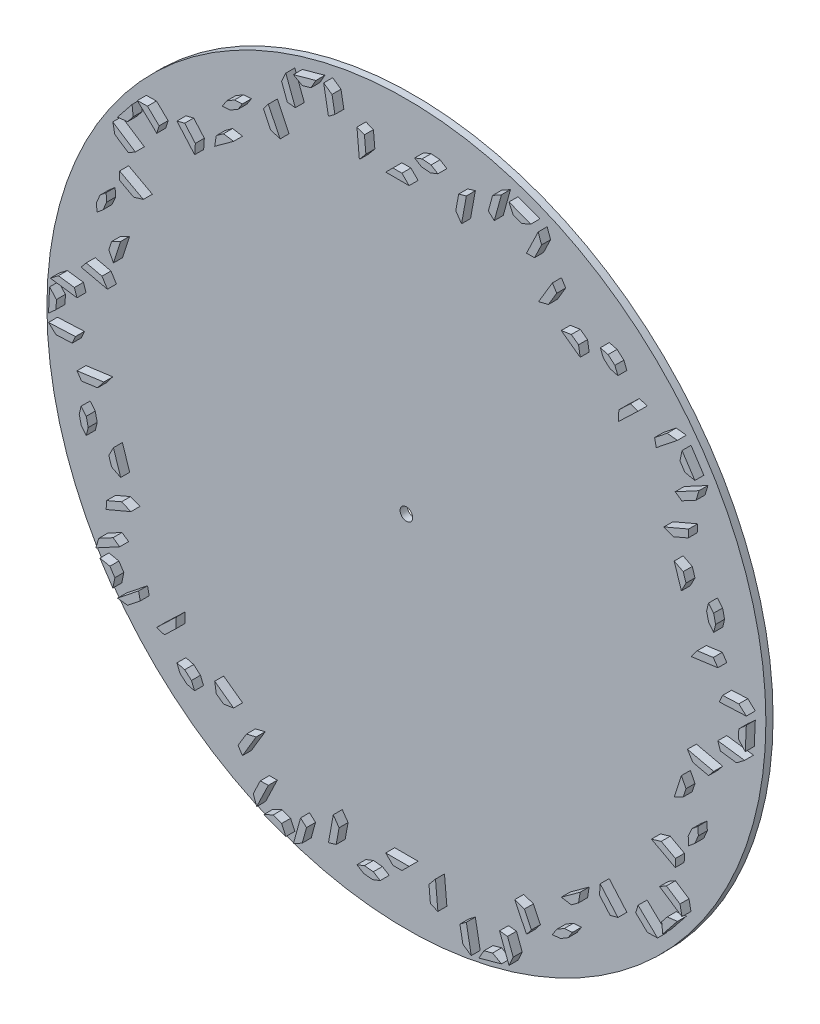
SolidWorks part; units mm, degrees
ref_plane "Front Plane" through (0, 0, 0) normal (0, 0, 1) x (1, 0, 0)
ref_plane "Top Plane" through (0, 0, 0) normal (0, 1, 0) x (1, 0, 0)
ref_plane "Right Plane" through (0, 0, 0) normal (1, 0, 0) x (0, 0, -1)
sketch "Sketch1" plane through (0, 0, 0) normal (0, 0, 1) x (1, 0, 0)
  circle A0 centre (0, 0) radius 100
  circle A1 centre (0, 0) radius 1.75
  dimension "D1" = 200
  dimension "D2" = 3.5
extrude "Boss-Extrude1" add sketch "Sketch1" along normal blind 2
sketch "Sketch3" plane through (0, 0, 2) normal (0, 0, 1) x (1, 0, 0)
  line L0 (0, 0) -> (0, -100) construction
  line L1 (1.25, -88.5) -> (3.25, -89.5)
  line L2 (-3.25, -82) -> (3.25, -82)
  line L3 (-3.25, -82) -> (-3.25, -97)
  line L4 (-3.25, -97) -> (3.25, -97)
  line L5 (3.25, -82) -> (3.25, -97)
  line L6 (-1.25, -84) -> (1.25, -84)
  line L7 (-1.25, -84) -> (-1.25, -95)
  line L8 (-1.25, -95) -> (1.25, -95)
  line L9 (1.25, -84) -> (1.25, -95)
  line L14 (-1.25, -88.5) -> (1.25, -88.5)
  line L15 (-1.25, -88.5) -> (-1.25, -90.5)
  line L16 (-1.25, -90.5) -> (1.25, -90.5)
  line L17 (1.25, -88.5) -> (1.25, -90.5)
  line L18 (3.25, -89.5) -> (1.25, -90.5)
  line L19 (-1.25, -88.5) -> (-3.25, -89.5)
  line L20 (-3.25, -89.5) -> (-1.25, -90.5)
  line L21 (1.25, -84) -> (3.25, -82)
  line L22 (-1.25, -84) -> (-3.25, -82)
  line L23 (1.25, -95) -> (3.25, -97)
  line L24 (-3.25, -97) -> (-1.25, -95)
  line L25 (-10.5873, -81.3786) -> (-4.1135, -81.9612)
  line L26 (-10.5873, -81.3786) -> (-11.9319, -96.3182)
  line L27 (-11.9319, -96.3182) -> (-5.4581, -96.9008)
  line L28 (-4.1135, -81.9612) -> (-5.4581, -96.9008)
  line L29 (-6.2847, -83.7739) -> (-4.1135, -81.9612)
  line L30 (-8.7747, -83.5498) -> (-10.5873, -81.3786)
  line L31 (-8.7747, -83.5498) -> (-9.7607, -94.5055)
  line L32 (-6.2847, -83.7739) -> (-7.2708, -94.7296)
  line L33 (-8.7747, -83.5498) -> (-6.2847, -83.7739)
  line L34 (-7.2708, -94.7296) -> (-5.4581, -96.9008)
  line L35 (-11.9319, -96.3182) -> (-9.7607, -94.5055)
  line L36 (-9.7607, -94.5055) -> (-7.2708, -94.7296)
  line L37 (-9.178, -88.0317) -> (-11.2596, -88.8484)
  line L38 (-11.2596, -88.8484) -> (-9.3573, -90.0236)
  line L39 (-9.178, -88.0317) -> (-6.6881, -88.2558)
  line L40 (-9.3573, -90.0236) -> (-6.8674, -90.2477)
  line L41 (-6.6881, -88.2558) -> (-4.7858, -89.431)
  line L42 (-4.7858, -89.431) -> (-6.8674, -90.2477)
  line L43 (-17.8394, -80.1019) -> (-11.4439, -81.2625)
  line L44 (-17.8394, -80.1019) -> (-20.5178, -94.8609)
  line L45 (-20.5178, -94.8609) -> (-14.1222, -96.0215)
  line L46 (-11.4439, -81.2625) -> (-14.1222, -96.0215)
  line L47 (-13.7689, -82.8733) -> (-11.4439, -81.2625)
  line L48 (-16.2287, -82.4269) -> (-17.8394, -80.1019)
  line L49 (-16.2287, -82.4269) -> (-18.1928, -93.2501)
  line L50 (-13.7689, -82.8733) -> (-15.733, -93.6965)
  line L51 (-16.2287, -82.4269) -> (-13.7689, -82.8733)
  line L52 (-15.733, -93.6965) -> (-14.1222, -96.0215)
  line L53 (-20.5178, -94.8609) -> (-18.1928, -93.2501)
  line L54 (-18.1928, -93.2501) -> (-15.733, -93.6965)
  line L55 (-17.0322, -86.8546) -> (-19.1786, -87.4814)
  line L56 (-19.1786, -87.4814) -> (-17.3893, -88.8224)
  line L57 (-17.0322, -86.8546) -> (-14.5724, -87.301)
  line L58 (-17.3893, -88.8224) -> (-14.9295, -89.2688)
  line L59 (-14.5724, -87.301) -> (-12.7831, -88.642)
  line L60 (-12.7831, -88.642) -> (-14.9295, -89.2688)
  line L61 (-24.9479, -78.1803) -> (-18.6821, -79.9096)
  line L62 (-24.9479, -78.1803) -> (-28.9385, -92.6398)
  line L63 (-28.9385, -92.6398) -> (-22.6727, -94.369)
  line L64 (-18.6821, -79.9096) -> (-22.6727, -94.369)
  line L65 (-21.1421, -81.3054) -> (-18.6821, -79.9096)
  line L66 (-23.552, -80.6403) -> (-24.9479, -78.1803)
  line L67 (-23.552, -80.6403) -> (-26.4785, -91.2439)
  line L68 (-21.1421, -81.3054) -> (-24.0685, -91.909)
  line L69 (-23.552, -80.6403) -> (-21.1421, -81.3054)
  line L70 (-24.0685, -91.909) -> (-22.6727, -94.369)
  line L71 (-28.9385, -92.6398) -> (-26.4785, -91.2439)
  line L72 (-26.4785, -91.2439) -> (-24.0685, -91.909)
  line L73 (-24.7492, -84.9782) -> (-26.9432, -85.4101)
  line L74 (-26.9432, -85.4101) -> (-25.2813, -86.9061)
  line L75 (-24.7492, -84.9782) -> (-22.3393, -85.6433)
  line L76 (-25.2813, -86.9061) -> (-22.8714, -87.5712)
  line L77 (-22.3393, -85.6433) -> (-20.6774, -87.1393)
  line L78 (-20.6774, -87.1393) -> (-22.8714, -87.5712)
  line L79 (-31.8555, -75.6293) -> (-25.77, -77.9132)
  line L80 (-31.8555, -75.6293) -> (-37.1261, -89.6728)
  line L81 (-37.1261, -89.6728) -> (-31.0406, -91.9568)
  line L82 (-25.77, -77.9132) -> (-31.0406, -91.9568)
  line L83 (-28.3452, -79.0829) -> (-25.77, -77.9132)
  line L84 (-30.6858, -78.2045) -> (-31.8555, -75.6293)
  line L85 (-30.6858, -78.2045) -> (-34.5509, -88.5031)
  line L86 (-28.3452, -79.0829) -> (-32.2103, -89.3815)
  line L87 (-30.6858, -78.2045) -> (-28.3452, -79.0829)
  line L88 (-32.2103, -89.3815) -> (-31.0406, -91.9568)
  line L89 (-37.1261, -89.6728) -> (-34.5509, -88.5031)
  line L90 (-34.5509, -88.5031) -> (-32.2103, -89.3815)
  line L91 (-32.267, -82.4176) -> (-34.4908, -82.6511)
  line L92 (-34.4908, -82.6511) -> (-32.9697, -84.29)
  line L93 (-32.267, -82.4176) -> (-29.9264, -83.296)
  line L94 (-32.9697, -84.29) -> (-30.6291, -85.1685)
  line L95 (-29.9264, -83.296) -> (-28.4053, -84.935)
  line L96 (-28.4053, -84.935) -> (-30.6291, -85.1685)
  line L97 (-38.5066, -72.4693) -> (-32.6503, -75.2896)
  line L98 (-38.5066, -72.4693) -> (-45.0149, -85.9839)
  line L99 (-45.0149, -85.9839) -> (-39.1586, -88.8041)
  line L100 (-32.6503, -75.2896) -> (-39.1586, -88.8041)
  line L101 (-35.32, -76.2237) -> (-32.6503, -75.2896)
  line L102 (-37.5724, -75.139) -> (-38.5066, -72.4693)
  line L103 (-37.5724, -75.139) -> (-42.3452, -85.0497)
  line L104 (-35.32, -76.2237) -> (-40.0927, -86.1344)
  line L105 (-37.5724, -75.139) -> (-35.32, -76.2237)
  line L106 (-40.0927, -86.1344) -> (-39.1586, -88.8041)
  line L107 (-45.0149, -85.9839) -> (-42.3452, -85.0497)
  line L108 (-42.3452, -85.0497) -> (-40.0927, -86.1344)
  line L109 (-39.5249, -79.1934) -> (-41.7607, -79.2266)
  line L110 (-41.7607, -79.2266) -> (-40.3927, -80.9953)
  line L111 (-39.5249, -79.1934) -> (-37.2725, -80.2781)
  line L112 (-40.3927, -80.9953) -> (-38.1403, -82.08)
  line L113 (-37.2725, -80.2781) -> (-35.9044, -82.0468)
  line L114 (-35.9044, -82.0468) -> (-38.1403, -82.08)
  line L115 (-44.8477, -68.7259) -> (-39.2678, -72.0597)
  line L116 (-44.8477, -68.7259) -> (-52.5412, -81.6026)
  line L117 (-52.5412, -81.6026) -> (-46.9613, -84.9365)
  line L118 (-39.2678, -72.0597) -> (-46.9613, -84.9365)
  line L119 (-42.0105, -72.7508) -> (-39.2678, -72.0597)
  line L120 (-44.1566, -71.4686) -> (-44.8477, -68.7259)
  line L121 (-44.1566, -71.4686) -> (-49.7985, -80.9115)
  line L122 (-42.0105, -72.7508) -> (-47.6524, -82.1938)
  line L123 (-44.1566, -71.4686) -> (-42.0105, -72.7508)
  line L124 (-47.6524, -82.1938) -> (-46.9613, -84.9365)
  line L125 (-52.5412, -81.6026) -> (-49.7985, -80.9115)
  line L126 (-49.7985, -80.9115) -> (-47.6524, -82.1938)
  line L127 (-46.4646, -75.3316) -> (-48.6944, -75.1642)
  line L128 (-48.6944, -75.1642) -> (-47.4904, -77.0485)
  line L129 (-46.4646, -75.3316) -> (-44.3185, -76.6138)
  line L130 (-47.4904, -77.0485) -> (-45.3443, -78.3307)
  line L131 (-44.3185, -76.6138) -> (-43.1145, -78.4981)
  line L132 (-43.1145, -78.4981) -> (-45.3443, -78.3307)
  line L133 (-50.8277, -64.4291) -> (-45.5691, -68.2497)
  line L134 (-50.8277, -64.4291) -> (-59.6445, -76.5643)
  line L135 (-59.6445, -76.5643) -> (-54.3859, -80.385)
  line L136 (-45.5691, -68.2497) -> (-54.3859, -80.385)
  line L137 (-48.3627, -68.6922) -> (-45.5691, -68.2497)
  line L138 (-50.3852, -67.2227) -> (-50.8277, -64.4291)
  line L139 (-50.3852, -67.2227) -> (-56.8509, -76.1219)
  line L140 (-48.3627, -68.6922) -> (-54.8283, -77.5913)
  line L141 (-50.3852, -67.2227) -> (-48.3627, -68.6922)
  line L142 (-54.8283, -77.5913) -> (-54.3859, -80.385)
  line L143 (-59.6445, -76.5643) -> (-56.8509, -76.1219)
  line L144 (-56.8509, -76.1219) -> (-54.8283, -77.5913)
  line L145 (-53.0303, -70.8633) -> (-55.2361, -70.4967)
  line L146 (-55.2361, -70.4967) -> (-54.2058, -72.4813)
  line L147 (-53.0303, -70.8633) -> (-51.0077, -72.3327)
  line L148 (-54.2058, -72.4813) -> (-52.1833, -73.9508)
  line L149 (-51.0077, -72.3327) -> (-49.9775, -74.3173)
  line L150 (-49.9775, -74.3173) -> (-52.1833, -73.9508)
  line L151 (-56.3985, -59.6136) -> (-51.5035, -63.8902)
  line L152 (-56.3985, -59.6136) -> (-66.2675, -70.9096)
  line L153 (-66.2675, -70.9096) -> (-61.3726, -75.1862)
  line L154 (-51.5035, -63.8902) -> (-61.3726, -75.1862)
  line L155 (-54.3255, -64.0804) -> (-51.5035, -63.8902)
  line L156 (-56.2082, -62.4356) -> (-56.3985, -59.6136)
  line L157 (-56.2082, -62.4356) -> (-63.4455, -70.7194)
  line L158 (-54.3255, -64.0804) -> (-61.5628, -72.3642)
  line L159 (-56.2082, -62.4356) -> (-54.3255, -64.0804)
  line L160 (-61.5628, -72.3642) -> (-61.3726, -75.1862)
  line L161 (-66.2675, -70.9096) -> (-63.4455, -70.7194)
  line L162 (-63.4455, -70.7194) -> (-61.5628, -72.3642)
  line L163 (-59.1689, -65.8244) -> (-61.333, -65.2616)
  line L164 (-61.333, -65.2616) -> (-60.4848, -67.3305)
  line L165 (-59.1689, -65.8244) -> (-57.2862, -67.4692)
  line L166 (-60.4848, -67.3305) -> (-58.6021, -68.9754)
  line L167 (-57.2862, -67.4692) -> (-56.438, -69.5382)
  line L168 (-56.438, -69.5382) -> (-58.6021, -68.9754)
  line L169 (-61.5151, -54.3181) -> (-57.0232, -59.0162)
  line L170 (-61.5151, -54.3181) -> (-72.3571, -64.684)
  line L171 (-72.3571, -64.684) -> (-67.8651, -69.3822)
  line L172 (-57.0232, -59.0162) -> (-67.8651, -69.3822)
  line L173 (-59.8509, -58.9528) -> (-57.0232, -59.0162)
  line L174 (-61.5786, -57.1458) -> (-61.5151, -54.3181)
  line L175 (-61.5786, -57.1458) -> (-69.5293, -64.7475)
  line L176 (-59.8509, -58.9528) -> (-67.8017, -66.5544)
  line L177 (-61.5786, -57.1458) -> (-59.8509, -58.9528)
  line L178 (-67.8017, -66.5544) -> (-67.8651, -69.3822)
  line L179 (-72.3571, -64.684) -> (-69.5293, -64.7475)
  line L180 (-69.5293, -64.7475) -> (-67.8017, -66.5544)
  line L181 (-64.8312, -60.2556) -> (-66.9361, -59.501)
  line L182 (-66.9361, -59.501) -> (-66.2768, -61.6377)
  line L183 (-64.8312, -60.2556) -> (-63.1035, -62.0625)
  line L184 (-66.2768, -61.6377) -> (-64.5491, -63.4447)
  line L185 (-63.1035, -62.0625) -> (-62.4442, -64.1992)
  line L186 (-62.4442, -64.1992) -> (-64.5491, -63.4447)
  line L187 (-66.1365, -48.5852) -> (-62.0838, -53.6671)
  line L188 (-66.1365, -48.5852) -> (-77.864, -57.9376)
  line L189 (-77.864, -57.9376) -> (-73.8113, -63.0195)
  line L190 (-62.0838, -53.6671) -> (-73.8113, -63.0195)
  line L191 (-64.8945, -53.3504) -> (-62.0838, -53.6671)
  line L192 (-66.4532, -51.3959) -> (-66.1365, -48.5852)
  line L193 (-66.4532, -51.3959) -> (-75.0534, -58.2542)
  line L194 (-64.8945, -53.3504) -> (-73.4946, -60.2088)
  line L195 (-66.4532, -51.3959) -> (-64.8945, -53.3504)
  line L196 (-73.4946, -60.2088) -> (-73.8113, -63.0195)
  line L197 (-77.864, -57.9376) -> (-75.0534, -58.2542)
  line L198 (-75.0534, -58.2542) -> (-73.4946, -60.2088)
  line L199 (-69.9714, -54.2016) -> (-72.0003, -53.2614)
  line L200 (-72.0003, -53.2614) -> (-71.5351, -55.4485)
  line L201 (-69.9714, -54.2016) -> (-68.4127, -56.1561)
  line L202 (-71.5351, -55.4485) -> (-69.9764, -57.4031)
  line L203 (-68.4127, -56.1561) -> (-67.9476, -58.3433)
  line L204 (-67.9476, -58.3433) -> (-69.9764, -57.4031)
  line L205 (-70.2254, -42.4612) -> (-66.6446, -47.8859)
  line L206 (-70.2254, -42.4612) -> (-82.744, -50.7246)
  line L207 (-82.744, -50.7246) -> (-79.1632, -56.1494)
  line L208 (-66.6446, -47.8859) -> (-79.1632, -56.1494)
  line L209 (-69.4155, -47.3186) -> (-66.6446, -47.8859)
  line L210 (-70.7928, -45.2321) -> (-70.2254, -42.4612)
  line L211 (-70.7928, -45.2321) -> (-79.9731, -51.292)
  line L212 (-69.4155, -47.3186) -> (-78.5958, -53.3784)
  line L213 (-70.7928, -45.2321) -> (-69.4155, -47.3186)
  line L214 (-78.5958, -53.3784) -> (-79.1632, -56.1494)
  line L215 (-82.744, -50.7246) -> (-79.9731, -51.292)
  line L216 (-79.9731, -51.292) -> (-78.5958, -53.3784)
  line L217 (-74.5484, -47.7112) -> (-76.4847, -46.5929)
  line L218 (-76.4847, -46.5929) -> (-76.2175, -48.813)
  line L219 (-74.5484, -47.7112) -> (-73.1711, -49.7976)
  line L220 (-76.2175, -48.813) -> (-74.8403, -50.8994)
  line L221 (-73.1711, -49.7976) -> (-72.9039, -52.0176)
  line L222 (-72.9039, -52.0176) -> (-74.8403, -50.8994)
  line L223 (-73.7489, -35.9953) -> (-70.6688, -41.7192)
  line L224 (-73.7489, -35.9953) -> (-86.9578, -43.1033)
  line L225 (-86.9578, -43.1033) -> (-83.8777, -48.8272)
  line L226 (-70.6688, -41.7192) -> (-83.8777, -48.8272)
  line L227 (-73.3777, -40.9057) -> (-70.6688, -41.7192)
  line L228 (-74.5624, -38.7042) -> (-73.7489, -35.9953)
  line L229 (-74.5624, -38.7042) -> (-84.2489, -43.9168)
  line L230 (-73.3777, -40.9057) -> (-83.0642, -46.1183)
  line L231 (-74.5624, -38.7042) -> (-73.3777, -40.9057)
  line L232 (-83.0642, -46.1183) -> (-83.8777, -48.8272)
  line L233 (-86.9578, -43.1033) -> (-84.2489, -43.9168)
  line L234 (-84.2489, -43.9168) -> (-83.0642, -46.1183)
  line L235 (-78.525, -40.8366) -> (-80.3534, -39.5493)
  line L236 (-80.3534, -39.5493) -> (-80.2862, -41.7844)
  line L237 (-78.525, -40.8366) -> (-77.3404, -43.0381)
  line L238 (-80.2862, -41.7844) -> (-79.1016, -43.9859)
  line L239 (-77.3404, -43.0381) -> (-77.2732, -45.2732)
  line L240 (-77.2732, -45.2732) -> (-79.1016, -43.9859)
  line L241 (-76.6786, -29.2396) -> (-74.1239, -35.2165)
  line L242 (-76.6786, -29.2396) -> (-90.4715, -35.135)
  line L243 (-90.4715, -35.135) -> (-87.9169, -41.1119)
  line L244 (-74.1239, -35.2165) -> (-87.9169, -41.1119)
  line L245 (-76.7491, -34.1635) -> (-74.1239, -35.2165)
  line L246 (-77.7316, -31.8647) -> (-76.6786, -29.2396)
  line L247 (-77.7316, -31.8647) -> (-87.8464, -36.188)
  line L248 (-76.7491, -34.1635) -> (-86.8639, -38.4868)
  line L249 (-77.7316, -31.8647) -> (-76.7491, -34.1635)
  line L250 (-86.8639, -38.4868) -> (-87.9169, -41.1119)
  line L251 (-90.4715, -35.135) -> (-87.8464, -36.188)
  line L252 (-87.8464, -36.188) -> (-86.8639, -38.4868)
  line L253 (-81.8695, -33.6333) -> (-83.5751, -32.1873)
  line L254 (-83.5751, -32.1873) -> (-83.7085, -34.4194)
  line L255 (-81.8695, -33.6333) -> (-80.8869, -35.9321)
  line L256 (-83.7085, -34.4194) -> (-82.726, -36.7182)
  line L257 (-80.8869, -35.9321) -> (-81.0204, -38.1642)
  line L258 (-81.0204, -38.1642) -> (-82.726, -36.7182)
  line L259 (-78.9909, -22.2485) -> (-76.9823, -28.4303)
  line L260 (-78.9909, -22.2485) -> (-93.2568, -26.8837)
  line L261 (-93.2568, -26.8837) -> (-91.2482, -33.0656)
  line L262 (-76.9823, -28.4303) -> (-91.2482, -33.0656)
  line L263 (-79.5025, -27.1462) -> (-76.9823, -28.4303)
  line L264 (-80.275, -24.7686) -> (-78.9909, -22.2485)
  line L265 (-80.275, -24.7686) -> (-90.7366, -28.1678)
  line L266 (-79.5025, -27.1462) -> (-89.9641, -30.5454)
  line L267 (-80.275, -24.7686) -> (-79.5025, -27.1462)
  line L268 (-89.9641, -30.5454) -> (-91.2482, -33.0656)
  line L269 (-93.2568, -26.8837) -> (-90.7366, -28.1678)
  line L270 (-90.7366, -28.1678) -> (-89.9641, -30.5454)
  line L271 (-84.5548, -26.1592) -> (-86.1239, -24.5661)
  line L272 (-86.1239, -24.5661) -> (-86.4569, -26.7772)
  line L273 (-84.5548, -26.1592) -> (-83.7822, -28.5368)
  line L274 (-86.4569, -26.7772) -> (-85.6843, -29.1549)
  line L275 (-83.7822, -28.5368) -> (-84.1153, -30.748)
  line L276 (-84.1153, -30.748) -> (-85.6843, -29.1549)
  line L277 (-80.6673, -15.0782) -> (-79.2209, -21.4152)
  line L278 (-80.6673, -15.0782) -> (-95.2912, -18.416)
  line L279 (-95.2912, -18.416) -> (-93.8448, -24.753)
  line L280 (-79.2209, -21.4152) -> (-93.8448, -24.753)
  line L281 (-81.6158, -19.9104) -> (-79.2209, -21.4152)
  line L282 (-82.1721, -17.4731) -> (-80.6673, -15.0782)
  line L283 (-82.1721, -17.4731) -> (-92.8963, -19.9208)
  line L284 (-81.6158, -19.9104) -> (-92.34, -22.3581)
  line L285 (-82.1721, -17.4731) -> (-81.6158, -19.9104)
  line L286 (-92.34, -22.3581) -> (-93.8448, -24.753)
  line L287 (-95.2912, -18.416) -> (-92.8963, -19.9208)
  line L288 (-92.8963, -19.9208) -> (-92.34, -22.3581)
  line L289 (-86.5593, -18.4744) -> (-87.9792, -16.7471)
  line L290 (-87.9792, -16.7471) -> (-88.5091, -18.9195)
  line L291 (-86.5593, -18.4744) -> (-86.003, -20.9118)
  line L292 (-88.5091, -18.9195) -> (-87.9528, -21.3568)
  line L293 (-86.003, -20.9118) -> (-86.5329, -23.0841)
  line L294 (-86.5329, -23.0841) -> (-87.9528, -21.3568)
  line L295 (-81.6941, -7.7865) -> (-80.8216, -14.2277)
  line L296 (-81.6941, -7.7865) -> (-96.5584, -9.8)
  line L297 (-96.5584, -9.8) -> (-95.6859, -16.2412)
  line L298 (-80.8216, -14.2277) -> (-95.6859, -16.2412)
  line L299 (-83.072, -12.5143) -> (-80.8216, -14.2277)
  line L300 (-83.4076, -10.0369) -> (-81.6941, -7.7865)
  line L301 (-83.4076, -10.0369) -> (-94.308, -11.5135)
  line L302 (-83.072, -12.5143) -> (-93.9724, -13.9908)
  line L303 (-83.4076, -10.0369) -> (-83.072, -12.5143)
  line L304 (-93.9724, -13.9908) -> (-95.6859, -16.2412)
  line L305 (-96.5584, -9.8) -> (-94.308, -11.5135)
  line L306 (-94.308, -11.5135) -> (-93.9724, -13.9908)
  line L307 (-87.8668, -10.641) -> (-89.1263, -8.7933)
  line L308 (-89.1263, -8.7933) -> (-89.8487, -10.9094)
  line L309 (-87.8668, -10.641) -> (-87.5313, -13.1183)
  line L310 (-89.8487, -10.9094) -> (-89.5132, -13.3868)
  line L311 (-87.5313, -13.1183) -> (-88.2537, -15.2345)
  line L312 (-88.2537, -15.2345) -> (-89.5132, -13.3868)
  line L313 (-82.0632, -0.4322) -> (-81.7716, -6.9256)
  line L314 (-82.0632, -0.4322) -> (-97.0481, -1.1052)
  line L315 (-97.0481, -1.1052) -> (-96.7565, -7.5986)
  line L316 (-81.7716, -6.9256) -> (-96.7565, -7.5986)
  line L317 (-83.8593, -5.0174) -> (-81.7716, -6.9256)
  line L318 (-83.9715, -2.5199) -> (-82.0632, -0.4322)
  line L319 (-83.9715, -2.5199) -> (-94.9604, -3.0134)
  line L320 (-83.8593, -5.0174) -> (-94.8483, -5.5109)
  line L321 (-83.9715, -2.5199) -> (-83.8593, -5.0174)
  line L322 (-94.8483, -5.5109) -> (-96.7565, -7.5986)
  line L323 (-97.0481, -1.1052) -> (-94.9604, -3.0134)
  line L324 (-94.9604, -3.0134) -> (-94.8483, -5.5109)
  line L325 (-88.467, -2.7218) -> (-89.5557, -0.7687)
  line L326 (-89.5557, -0.7687) -> (-90.465, -2.8115)
  line L327 (-88.467, -2.7218) -> (-88.3548, -5.2193)
  line L328 (-90.465, -2.8115) -> (-90.3528, -5.309)
  line L329 (-88.3548, -5.2193) -> (-89.2641, -7.2621)
  line L330 (-89.2641, -7.2621) -> (-90.3528, -5.309)
  line L331 (-81.7716, 6.9256) -> (-82.0632, 0.4322)
  line L332 (-81.7716, 6.9256) -> (-96.7565, 7.5986)
  line L333 (-96.7565, 7.5986) -> (-97.0481, 1.1052)
  line L334 (-82.0632, 0.4322) -> (-97.0481, 1.1052)
  line L335 (-83.9715, 2.5199) -> (-82.0632, 0.4322)
  line L336 (-83.8593, 5.0174) -> (-81.7716, 6.9256)
  line L337 (-83.8593, 5.0174) -> (-94.8483, 5.5109)
  line L338 (-83.9715, 2.5199) -> (-94.9604, 3.0134)
  line L339 (-83.8593, 5.0174) -> (-83.9715, 2.5199)
  line L340 (-94.9604, 3.0134) -> (-97.0481, 1.1052)
  line L341 (-96.7565, 7.5986) -> (-94.8483, 5.5109)
  line L342 (-94.8483, 5.5109) -> (-94.9604, 3.0134)
  line L343 (-88.3548, 5.2193) -> (-89.2641, 7.2621)
  line L344 (-89.2641, 7.2621) -> (-90.3528, 5.309)
  line L345 (-88.3548, 5.2193) -> (-88.467, 2.7218)
  line L346 (-90.3528, 5.309) -> (-90.465, 2.8115)
  line L347 (-88.467, 2.7218) -> (-89.5557, 0.7687)
  line L348 (-89.5557, 0.7687) -> (-90.465, 2.8115)
  line L349 (-80.8216, 14.2277) -> (-81.6941, 7.7865)
  line L350 (-80.8216, 14.2277) -> (-95.6859, 16.2412)
  line L351 (-95.6859, 16.2412) -> (-96.5584, 9.8)
  line L352 (-81.6941, 7.7865) -> (-96.5584, 9.8)
  line L353 (-83.4076, 10.0369) -> (-81.6941, 7.7865)
  line L354 (-83.072, 12.5143) -> (-80.8216, 14.2277)
  line L355 (-83.072, 12.5143) -> (-93.9724, 13.9908)
  line L356 (-83.4076, 10.0369) -> (-94.308, 11.5135)
  line L357 (-83.072, 12.5143) -> (-83.4076, 10.0369)
  line L358 (-94.308, 11.5135) -> (-96.5584, 9.8)
  line L359 (-95.6859, 16.2412) -> (-93.9724, 13.9908)
  line L360 (-93.9724, 13.9908) -> (-94.308, 11.5135)
  line L361 (-87.5313, 13.1183) -> (-88.2537, 15.2345)
  line L362 (-88.2537, 15.2345) -> (-89.5132, 13.3868)
  line L363 (-87.5313, 13.1183) -> (-87.8668, 10.641)
  line L364 (-89.5132, 13.3868) -> (-89.8487, 10.9094)
  line L365 (-87.8668, 10.641) -> (-89.1263, 8.7933)
  line L366 (-89.1263, 8.7933) -> (-89.8487, 10.9094)
  line L367 (-79.2209, 21.4152) -> (-80.6673, 15.0782)
  line L368 (-79.2209, 21.4152) -> (-93.8448, 24.753)
  line L369 (-93.8448, 24.753) -> (-95.2912, 18.416)
  line L370 (-80.6673, 15.0782) -> (-95.2912, 18.416)
  line L371 (-82.1721, 17.4731) -> (-80.6673, 15.0782)
  line L372 (-81.6158, 19.9104) -> (-79.2209, 21.4152)
  line L373 (-81.6158, 19.9104) -> (-92.34, 22.3581)
  line L374 (-82.1721, 17.4731) -> (-92.8963, 19.9208)
  line L375 (-81.6158, 19.9104) -> (-82.1721, 17.4731)
  line L376 (-92.8963, 19.9208) -> (-95.2912, 18.416)
  line L377 (-93.8448, 24.753) -> (-92.34, 22.3581)
  line L378 (-92.34, 22.3581) -> (-92.8963, 19.9208)
  line L379 (-86.003, 20.9118) -> (-86.5329, 23.0841)
  line L380 (-86.5329, 23.0841) -> (-87.9528, 21.3568)
  line L381 (-86.003, 20.9118) -> (-86.5593, 18.4744)
  line L382 (-87.9528, 21.3568) -> (-88.5091, 18.9195)
  line L383 (-86.5593, 18.4744) -> (-87.9792, 16.7471)
  line L384 (-87.9792, 16.7471) -> (-88.5091, 18.9195)
  line L385 (-76.9823, 28.4303) -> (-78.9909, 22.2485)
  line L386 (-76.9823, 28.4303) -> (-91.2482, 33.0656)
  line L387 (-91.2482, 33.0656) -> (-93.2568, 26.8837)
  line L388 (-78.9909, 22.2485) -> (-93.2568, 26.8837)
  line L389 (-80.275, 24.7686) -> (-78.9909, 22.2485)
  line L390 (-79.5025, 27.1462) -> (-76.9823, 28.4303)
  line L391 (-79.5025, 27.1462) -> (-89.9641, 30.5454)
  line L392 (-80.275, 24.7686) -> (-90.7366, 28.1678)
  line L393 (-79.5025, 27.1462) -> (-80.275, 24.7686)
  line L394 (-90.7366, 28.1678) -> (-93.2568, 26.8837)
  line L395 (-91.2482, 33.0656) -> (-89.9641, 30.5454)
  line L396 (-89.9641, 30.5454) -> (-90.7366, 28.1678)
  line L397 (-83.7822, 28.5368) -> (-84.1153, 30.748)
  line L398 (-84.1153, 30.748) -> (-85.6843, 29.1549)
  line L399 (-83.7822, 28.5368) -> (-84.5548, 26.1592)
  line L400 (-85.6843, 29.1549) -> (-86.4569, 26.7772)
  line L401 (-84.5548, 26.1592) -> (-86.1239, 24.5661)
  line L402 (-86.1239, 24.5661) -> (-86.4569, 26.7772)
  line L403 (-74.1239, 35.2165) -> (-76.6786, 29.2396)
  line L404 (-74.1239, 35.2165) -> (-87.9169, 41.1119)
  line L405 (-87.9169, 41.1119) -> (-90.4715, 35.135)
  line L406 (-76.6786, 29.2396) -> (-90.4715, 35.135)
  line L407 (-77.7316, 31.8647) -> (-76.6786, 29.2396)
  line L408 (-76.7491, 34.1635) -> (-74.1239, 35.2165)
  line L409 (-76.7491, 34.1635) -> (-86.8639, 38.4868)
  line L410 (-77.7316, 31.8647) -> (-87.8464, 36.188)
  line L411 (-76.7491, 34.1635) -> (-77.7316, 31.8647)
  line L412 (-87.8464, 36.188) -> (-90.4715, 35.135)
  line L413 (-87.9169, 41.1119) -> (-86.8639, 38.4868)
  line L414 (-86.8639, 38.4868) -> (-87.8464, 36.188)
  line L415 (-80.8869, 35.9321) -> (-81.0204, 38.1642)
  line L416 (-81.0204, 38.1642) -> (-82.726, 36.7182)
  line L417 (-80.8869, 35.9321) -> (-81.8695, 33.6333)
  line L418 (-82.726, 36.7182) -> (-83.7085, 34.4194)
  line L419 (-81.8695, 33.6333) -> (-83.5751, 32.1873)
  line L420 (-83.5751, 32.1873) -> (-83.7085, 34.4194)
  line L421 (-70.6688, 41.7192) -> (-73.7489, 35.9953)
  line L422 (-70.6688, 41.7192) -> (-83.8777, 48.8272)
  line L423 (-83.8777, 48.8272) -> (-86.9578, 43.1033)
  line L424 (-73.7489, 35.9953) -> (-86.9578, 43.1033)
  line L425 (-74.5624, 38.7042) -> (-73.7489, 35.9953)
  line L426 (-73.3777, 40.9057) -> (-70.6688, 41.7192)
  line L427 (-73.3777, 40.9057) -> (-83.0642, 46.1183)
  line L428 (-74.5624, 38.7042) -> (-84.2489, 43.9168)
  line L429 (-73.3777, 40.9057) -> (-74.5624, 38.7042)
  line L430 (-84.2489, 43.9168) -> (-86.9578, 43.1033)
  line L431 (-83.8777, 48.8272) -> (-83.0642, 46.1183)
  line L432 (-83.0642, 46.1183) -> (-84.2489, 43.9168)
  line L433 (-77.3404, 43.0381) -> (-77.2732, 45.2732)
  line L434 (-77.2732, 45.2732) -> (-79.1016, 43.9859)
  line L435 (-77.3404, 43.0381) -> (-78.525, 40.8366)
  line L436 (-79.1016, 43.9859) -> (-80.2862, 41.7844)
  line L437 (-78.525, 40.8366) -> (-80.3534, 39.5493)
  line L438 (-80.3534, 39.5493) -> (-80.2862, 41.7844)
  line L439 (-66.6446, 47.8859) -> (-70.2254, 42.4612)
  line L440 (-66.6446, 47.8859) -> (-79.1632, 56.1494)
  line L441 (-79.1632, 56.1494) -> (-82.744, 50.7246)
  line L442 (-70.2254, 42.4612) -> (-82.744, 50.7246)
  line L443 (-70.7928, 45.2321) -> (-70.2254, 42.4612)
  line L444 (-69.4155, 47.3186) -> (-66.6446, 47.8859)
  line L445 (-69.4155, 47.3186) -> (-78.5958, 53.3784)
  line L446 (-70.7928, 45.2321) -> (-79.9731, 51.292)
  line L447 (-69.4155, 47.3186) -> (-70.7928, 45.2321)
  line L448 (-79.9731, 51.292) -> (-82.744, 50.7246)
  line L449 (-79.1632, 56.1494) -> (-78.5958, 53.3784)
  line L450 (-78.5958, 53.3784) -> (-79.9731, 51.292)
  line L451 (-73.1711, 49.7976) -> (-72.9039, 52.0176)
  line L452 (-72.9039, 52.0176) -> (-74.8403, 50.8994)
  line L453 (-73.1711, 49.7976) -> (-74.5484, 47.7112)
  line L454 (-74.8403, 50.8994) -> (-76.2175, 48.813)
  line L455 (-74.5484, 47.7112) -> (-76.4847, 46.5929)
  line L456 (-76.4847, 46.5929) -> (-76.2175, 48.813)
  line L457 (-62.0838, 53.6671) -> (-66.1365, 48.5852)
  line L458 (-62.0838, 53.6671) -> (-73.8113, 63.0195)
  line L459 (-73.8113, 63.0195) -> (-77.864, 57.9376)
  line L460 (-66.1365, 48.5852) -> (-77.864, 57.9376)
  line L461 (-66.4532, 51.3959) -> (-66.1365, 48.5852)
  line L462 (-64.8945, 53.3504) -> (-62.0838, 53.6671)
  line L463 (-64.8945, 53.3504) -> (-73.4946, 60.2088)
  line L464 (-66.4532, 51.3959) -> (-75.0534, 58.2542)
  line L465 (-64.8945, 53.3504) -> (-66.4532, 51.3959)
  line L466 (-75.0534, 58.2542) -> (-77.864, 57.9376)
  line L467 (-73.8113, 63.0195) -> (-73.4946, 60.2088)
  line L468 (-73.4946, 60.2088) -> (-75.0534, 58.2542)
  line L469 (-68.4127, 56.1561) -> (-67.9476, 58.3433)
  line L470 (-67.9476, 58.3433) -> (-69.9764, 57.4031)
  line L471 (-68.4127, 56.1561) -> (-69.9714, 54.2016)
  line L472 (-69.9764, 57.4031) -> (-71.5351, 55.4485)
  line L473 (-69.9714, 54.2016) -> (-72.0003, 53.2614)
  line L474 (-72.0003, 53.2614) -> (-71.5351, 55.4485)
  line L475 (-57.0232, 59.0162) -> (-61.5151, 54.3181)
  line L476 (-57.0232, 59.0162) -> (-67.8651, 69.3822)
  line L477 (-67.8651, 69.3822) -> (-72.3571, 64.684)
  line L478 (-61.5151, 54.3181) -> (-72.3571, 64.684)
  line L479 (-61.5786, 57.1458) -> (-61.5151, 54.3181)
  line L480 (-59.8509, 58.9528) -> (-57.0232, 59.0162)
  line L481 (-59.8509, 58.9528) -> (-67.8017, 66.5544)
  line L482 (-61.5786, 57.1458) -> (-69.5293, 64.7475)
  line L483 (-59.8509, 58.9528) -> (-61.5786, 57.1458)
  line L484 (-69.5293, 64.7475) -> (-72.3571, 64.684)
  line L485 (-67.8651, 69.3822) -> (-67.8017, 66.5544)
  line L486 (-67.8017, 66.5544) -> (-69.5293, 64.7475)
  line L487 (-63.1035, 62.0625) -> (-62.4442, 64.1992)
  line L488 (-62.4442, 64.1992) -> (-64.5491, 63.4447)
  line L489 (-63.1035, 62.0625) -> (-64.8312, 60.2556)
  line L490 (-64.5491, 63.4447) -> (-66.2768, 61.6377)
  line L491 (-64.8312, 60.2556) -> (-66.9361, 59.501)
  line L492 (-66.9361, 59.501) -> (-66.2768, 61.6377)
  line L493 (-51.5035, 63.8902) -> (-56.3985, 59.6136)
  line L494 (-51.5035, 63.8902) -> (-61.3726, 75.1862)
  line L495 (-61.3726, 75.1862) -> (-66.2675, 70.9096)
  line L496 (-56.3985, 59.6136) -> (-66.2675, 70.9096)
  line L497 (-56.2082, 62.4356) -> (-56.3985, 59.6136)
  line L498 (-54.3255, 64.0804) -> (-51.5035, 63.8902)
  line L499 (-54.3255, 64.0804) -> (-61.5628, 72.3642)
  line L500 (-56.2082, 62.4356) -> (-63.4455, 70.7194)
  line L501 (-54.3255, 64.0804) -> (-56.2082, 62.4356)
  line L502 (-63.4455, 70.7194) -> (-66.2675, 70.9096)
  line L503 (-61.3726, 75.1862) -> (-61.5628, 72.3642)
  line L504 (-61.5628, 72.3642) -> (-63.4455, 70.7194)
  line L505 (-57.2862, 67.4692) -> (-56.438, 69.5382)
  line L506 (-56.438, 69.5382) -> (-58.6021, 68.9754)
  line L507 (-57.2862, 67.4692) -> (-59.1689, 65.8244)
  line L508 (-58.6021, 68.9754) -> (-60.4848, 67.3305)
  line L509 (-59.1689, 65.8244) -> (-61.333, 65.2616)
  line L510 (-61.333, 65.2616) -> (-60.4848, 67.3305)
  line L511 (-45.5691, 68.2497) -> (-50.8277, 64.4291)
  line L512 (-45.5691, 68.2497) -> (-54.3859, 80.385)
  line L513 (-54.3859, 80.385) -> (-59.6445, 76.5643)
  line L514 (-50.8277, 64.4291) -> (-59.6445, 76.5643)
  line L515 (-50.3852, 67.2227) -> (-50.8277, 64.4291)
  line L516 (-48.3627, 68.6922) -> (-45.5691, 68.2497)
  line L517 (-48.3627, 68.6922) -> (-54.8283, 77.5913)
  line L518 (-50.3852, 67.2227) -> (-56.8509, 76.1219)
  line L519 (-48.3627, 68.6922) -> (-50.3852, 67.2227)
  line L520 (-56.8509, 76.1219) -> (-59.6445, 76.5643)
  line L521 (-54.3859, 80.385) -> (-54.8283, 77.5913)
  line L522 (-54.8283, 77.5913) -> (-56.8509, 76.1219)
  line L523 (-51.0077, 72.3327) -> (-49.9775, 74.3173)
  line L524 (-49.9775, 74.3173) -> (-52.1833, 73.9508)
  line L525 (-51.0077, 72.3327) -> (-53.0303, 70.8633)
  line L526 (-52.1833, 73.9508) -> (-54.2058, 72.4813)
  line L527 (-53.0303, 70.8633) -> (-55.2361, 70.4967)
  line L528 (-55.2361, 70.4967) -> (-54.2058, 72.4813)
  line L529 (-39.2678, 72.0597) -> (-44.8477, 68.7259)
  line L530 (-39.2678, 72.0597) -> (-46.9613, 84.9365)
  line L531 (-46.9613, 84.9365) -> (-52.5412, 81.6026)
  line L532 (-44.8477, 68.7259) -> (-52.5412, 81.6026)
  line L533 (-44.1566, 71.4686) -> (-44.8477, 68.7259)
  line L534 (-42.0105, 72.7508) -> (-39.2678, 72.0597)
  line L535 (-42.0105, 72.7508) -> (-47.6524, 82.1938)
  line L536 (-44.1566, 71.4686) -> (-49.7985, 80.9115)
  line L537 (-42.0105, 72.7508) -> (-44.1566, 71.4686)
  line L538 (-49.7985, 80.9115) -> (-52.5412, 81.6026)
  line L539 (-46.9613, 84.9365) -> (-47.6524, 82.1938)
  line L540 (-47.6524, 82.1938) -> (-49.7985, 80.9115)
  line L541 (-44.3185, 76.6138) -> (-43.1145, 78.4981)
  line L542 (-43.1145, 78.4981) -> (-45.3443, 78.3307)
  line L543 (-44.3185, 76.6138) -> (-46.4646, 75.3316)
  line L544 (-45.3443, 78.3307) -> (-47.4904, 77.0485)
  line L545 (-46.4646, 75.3316) -> (-48.6944, 75.1642)
  line L546 (-48.6944, 75.1642) -> (-47.4904, 77.0485)
  line L547 (-32.6503, 75.2896) -> (-38.5066, 72.4693)
  line L548 (-32.6503, 75.2896) -> (-39.1586, 88.8041)
  line L549 (-39.1586, 88.8041) -> (-45.0149, 85.9839)
  line L550 (-38.5066, 72.4693) -> (-45.0149, 85.9839)
  line L551 (-37.5724, 75.139) -> (-38.5066, 72.4693)
  line L552 (-35.32, 76.2237) -> (-32.6503, 75.2896)
  line L553 (-35.32, 76.2237) -> (-40.0927, 86.1344)
  line L554 (-37.5724, 75.139) -> (-42.3452, 85.0497)
  line L555 (-35.32, 76.2237) -> (-37.5724, 75.139)
  line L556 (-42.3452, 85.0497) -> (-45.0149, 85.9839)
  line L557 (-39.1586, 88.8041) -> (-40.0927, 86.1344)
  line L558 (-40.0927, 86.1344) -> (-42.3452, 85.0497)
  line L559 (-37.2725, 80.2781) -> (-35.9044, 82.0468)
  line L560 (-35.9044, 82.0468) -> (-38.1403, 82.08)
  line L561 (-37.2725, 80.2781) -> (-39.5249, 79.1934)
  line L562 (-38.1403, 82.08) -> (-40.3927, 80.9953)
  line L563 (-39.5249, 79.1934) -> (-41.7607, 79.2266)
  line L564 (-41.7607, 79.2266) -> (-40.3927, 80.9953)
  line L565 (-25.77, 77.9132) -> (-31.8555, 75.6293)
  line L566 (-25.77, 77.9132) -> (-31.0406, 91.9568)
  line L567 (-31.0406, 91.9568) -> (-37.1261, 89.6728)
  line L568 (-31.8555, 75.6293) -> (-37.1261, 89.6728)
  line L569 (-30.6858, 78.2045) -> (-31.8555, 75.6293)
  line L570 (-28.3452, 79.0829) -> (-25.77, 77.9132)
  line L571 (-28.3452, 79.0829) -> (-32.2103, 89.3815)
  line L572 (-30.6858, 78.2045) -> (-34.5509, 88.5031)
  line L573 (-28.3452, 79.0829) -> (-30.6858, 78.2045)
  line L574 (-34.5509, 88.5031) -> (-37.1261, 89.6728)
  line L575 (-31.0406, 91.9568) -> (-32.2103, 89.3815)
  line L576 (-32.2103, 89.3815) -> (-34.5509, 88.5031)
  line L577 (-29.9264, 83.296) -> (-28.4053, 84.935)
  line L578 (-28.4053, 84.935) -> (-30.6291, 85.1685)
  line L579 (-29.9264, 83.296) -> (-32.267, 82.4176)
  line L580 (-30.6291, 85.1685) -> (-32.9697, 84.29)
  line L581 (-32.267, 82.4176) -> (-34.4908, 82.6511)
  line L582 (-34.4908, 82.6511) -> (-32.9697, 84.29)
  line L583 (-18.6821, 79.9096) -> (-24.9479, 78.1803)
  line L584 (-18.6821, 79.9096) -> (-22.6727, 94.369)
  line L585 (-22.6727, 94.369) -> (-28.9385, 92.6398)
  line L586 (-24.9479, 78.1803) -> (-28.9385, 92.6398)
  line L587 (-23.552, 80.6403) -> (-24.9479, 78.1803)
  line L588 (-21.1421, 81.3054) -> (-18.6821, 79.9096)
  line L589 (-21.1421, 81.3054) -> (-24.0685, 91.909)
  line L590 (-23.552, 80.6403) -> (-26.4785, 91.2439)
  line L591 (-21.1421, 81.3054) -> (-23.552, 80.6403)
  line L592 (-26.4785, 91.2439) -> (-28.9385, 92.6398)
  line L593 (-22.6727, 94.369) -> (-24.0685, 91.909)
  line L594 (-24.0685, 91.909) -> (-26.4785, 91.2439)
  line L595 (-22.3393, 85.6433) -> (-20.6774, 87.1393)
  line L596 (-20.6774, 87.1393) -> (-22.8714, 87.5712)
  line L597 (-22.3393, 85.6433) -> (-24.7492, 84.9782)
  line L598 (-22.8714, 87.5712) -> (-25.2813, 86.9061)
  line L599 (-24.7492, 84.9782) -> (-26.9432, 85.4101)
  line L600 (-26.9432, 85.4101) -> (-25.2813, 86.9061)
  line L601 (-11.4439, 81.2625) -> (-17.8394, 80.1019)
  line L602 (-11.4439, 81.2625) -> (-14.1222, 96.0215)
  line L603 (-14.1222, 96.0215) -> (-20.5178, 94.8609)
  line L604 (-17.8394, 80.1019) -> (-20.5178, 94.8609)
  line L605 (-16.2287, 82.4269) -> (-17.8394, 80.1019)
  line L606 (-13.7689, 82.8733) -> (-11.4439, 81.2625)
  line L607 (-13.7689, 82.8733) -> (-15.733, 93.6965)
  line L608 (-16.2287, 82.4269) -> (-18.1928, 93.2501)
  line L609 (-13.7689, 82.8733) -> (-16.2287, 82.4269)
  line L610 (-18.1928, 93.2501) -> (-20.5178, 94.8609)
  line L611 (-14.1222, 96.0215) -> (-15.733, 93.6965)
  line L612 (-15.733, 93.6965) -> (-18.1928, 93.2501)
  line L613 (-14.5724, 87.301) -> (-12.7831, 88.642)
  line L614 (-12.7831, 88.642) -> (-14.9295, 89.2688)
  line L615 (-14.5724, 87.301) -> (-17.0322, 86.8546)
  line L616 (-14.9295, 89.2688) -> (-17.3893, 88.8224)
  line L617 (-17.0322, 86.8546) -> (-19.1786, 87.4814)
  line L618 (-19.1786, 87.4814) -> (-17.3893, 88.8224)
  line L619 (-4.1135, 81.9612) -> (-10.5873, 81.3786)
  line L620 (-4.1135, 81.9612) -> (-5.4581, 96.9008)
  line L621 (-5.4581, 96.9008) -> (-11.9319, 96.3182)
  line L622 (-10.5873, 81.3786) -> (-11.9319, 96.3182)
  line L623 (-8.7747, 83.5498) -> (-10.5873, 81.3786)
  line L624 (-6.2847, 83.7739) -> (-4.1135, 81.9612)
  line L625 (-6.2847, 83.7739) -> (-7.2708, 94.7296)
  line L626 (-8.7747, 83.5498) -> (-9.7607, 94.5055)
  line L627 (-6.2847, 83.7739) -> (-8.7747, 83.5498)
  line L628 (-9.7607, 94.5055) -> (-11.9319, 96.3182)
  line L629 (-5.4581, 96.9008) -> (-7.2708, 94.7296)
  line L630 (-7.2708, 94.7296) -> (-9.7607, 94.5055)
  line L631 (-6.6881, 88.2558) -> (-4.7858, 89.431)
  line L632 (-4.7858, 89.431) -> (-6.8674, 90.2477)
  line L633 (-6.6881, 88.2558) -> (-9.178, 88.0317)
  line L634 (-6.8674, 90.2477) -> (-9.3573, 90.0236)
  line L635 (-9.178, 88.0317) -> (-11.2596, 88.8484)
  line L636 (-11.2596, 88.8484) -> (-9.3573, 90.0236)
  line L637 (3.25, 82) -> (-3.25, 82)
  line L638 (3.25, 82) -> (3.25, 97)
  line L639 (3.25, 97) -> (-3.25, 97)
  line L640 (-3.25, 82) -> (-3.25, 97)
  line L641 (-1.25, 84) -> (-3.25, 82)
  line L642 (1.25, 84) -> (3.25, 82)
  line L643 (1.25, 84) -> (1.25, 95)
  line L644 (-1.25, 84) -> (-1.25, 95)
  line L645 (1.25, 84) -> (-1.25, 84)
  line L646 (-1.25, 95) -> (-3.25, 97)
  line L647 (3.25, 97) -> (1.25, 95)
  line L648 (1.25, 95) -> (-1.25, 95)
  line L649 (1.25, 88.5) -> (3.25, 89.5)
  line L650 (3.25, 89.5) -> (1.25, 90.5)
  line L651 (1.25, 88.5) -> (-1.25, 88.5)
  line L652 (1.25, 90.5) -> (-1.25, 90.5)
  line L653 (-1.25, 88.5) -> (-3.25, 89.5)
  line L654 (-3.25, 89.5) -> (-1.25, 90.5)
  line L655 (10.5873, 81.3786) -> (4.1135, 81.9612)
  line L656 (10.5873, 81.3786) -> (11.9319, 96.3182)
  line L657 (11.9319, 96.3182) -> (5.4581, 96.9008)
  line L658 (4.1135, 81.9612) -> (5.4581, 96.9008)
  line L659 (6.2847, 83.7739) -> (4.1135, 81.9612)
  line L660 (8.7747, 83.5498) -> (10.5873, 81.3786)
  line L661 (8.7747, 83.5498) -> (9.7607, 94.5055)
  line L662 (6.2847, 83.7739) -> (7.2708, 94.7296)
  line L663 (8.7747, 83.5498) -> (6.2847, 83.7739)
  line L664 (7.2708, 94.7296) -> (5.4581, 96.9008)
  line L665 (11.9319, 96.3182) -> (9.7607, 94.5055)
  line L666 (9.7607, 94.5055) -> (7.2708, 94.7296)
  line L667 (9.178, 88.0317) -> (11.2596, 88.8484)
  line L668 (11.2596, 88.8484) -> (9.3573, 90.0236)
  line L669 (9.178, 88.0317) -> (6.6881, 88.2558)
  line L670 (9.3573, 90.0236) -> (6.8674, 90.2477)
  line L671 (6.6881, 88.2558) -> (4.7858, 89.431)
  line L672 (4.7858, 89.431) -> (6.8674, 90.2477)
  line L673 (17.8394, 80.1019) -> (11.4439, 81.2625)
  line L674 (17.8394, 80.1019) -> (20.5178, 94.8609)
  line L675 (20.5178, 94.8609) -> (14.1222, 96.0215)
  line L676 (11.4439, 81.2625) -> (14.1222, 96.0215)
  line L677 (13.7689, 82.8733) -> (11.4439, 81.2625)
  line L678 (16.2287, 82.4269) -> (17.8394, 80.1019)
  line L679 (16.2287, 82.4269) -> (18.1928, 93.2501)
  line L680 (13.7689, 82.8733) -> (15.733, 93.6965)
  line L681 (16.2287, 82.4269) -> (13.7689, 82.8733)
  line L682 (15.733, 93.6965) -> (14.1222, 96.0215)
  line L683 (20.5178, 94.8609) -> (18.1928, 93.2501)
  line L684 (18.1928, 93.2501) -> (15.733, 93.6965)
  line L685 (17.0322, 86.8546) -> (19.1786, 87.4814)
  line L686 (19.1786, 87.4814) -> (17.3893, 88.8224)
  line L687 (17.0322, 86.8546) -> (14.5724, 87.301)
  line L688 (17.3893, 88.8224) -> (14.9295, 89.2688)
  line L689 (14.5724, 87.301) -> (12.7831, 88.642)
  line L690 (12.7831, 88.642) -> (14.9295, 89.2688)
  line L691 (24.9479, 78.1803) -> (18.6821, 79.9096)
  line L692 (24.9479, 78.1803) -> (28.9385, 92.6398)
  line L693 (28.9385, 92.6398) -> (22.6727, 94.369)
  line L694 (18.6821, 79.9096) -> (22.6727, 94.369)
  line L695 (21.1421, 81.3054) -> (18.6821, 79.9096)
  line L696 (23.552, 80.6403) -> (24.9479, 78.1803)
  line L697 (23.552, 80.6403) -> (26.4785, 91.2439)
  line L698 (21.1421, 81.3054) -> (24.0685, 91.909)
  line L699 (23.552, 80.6403) -> (21.1421, 81.3054)
  line L700 (24.0685, 91.909) -> (22.6727, 94.369)
  line L701 (28.9385, 92.6398) -> (26.4785, 91.2439)
  line L702 (26.4785, 91.2439) -> (24.0685, 91.909)
  line L703 (24.7492, 84.9782) -> (26.9432, 85.4101)
  line L704 (26.9432, 85.4101) -> (25.2813, 86.9061)
  line L705 (24.7492, 84.9782) -> (22.3393, 85.6433)
  line L706 (25.2813, 86.9061) -> (22.8714, 87.5712)
  line L707 (22.3393, 85.6433) -> (20.6774, 87.1393)
  line L708 (20.6774, 87.1393) -> (22.8714, 87.5712)
  line L709 (31.8555, 75.6293) -> (25.77, 77.9132)
  line L710 (31.8555, 75.6293) -> (37.1261, 89.6728)
  line L711 (37.1261, 89.6728) -> (31.0406, 91.9568)
  line L712 (25.77, 77.9132) -> (31.0406, 91.9568)
  line L713 (28.3452, 79.0829) -> (25.77, 77.9132)
  line L714 (30.6858, 78.2045) -> (31.8555, 75.6293)
  line L715 (30.6858, 78.2045) -> (34.5509, 88.5031)
  line L716 (28.3452, 79.0829) -> (32.2103, 89.3815)
  line L717 (30.6858, 78.2045) -> (28.3452, 79.0829)
  line L718 (32.2103, 89.3815) -> (31.0406, 91.9568)
  line L719 (37.1261, 89.6728) -> (34.5509, 88.5031)
  line L720 (34.5509, 88.5031) -> (32.2103, 89.3815)
  line L721 (32.267, 82.4176) -> (34.4908, 82.6511)
  line L722 (34.4908, 82.6511) -> (32.9697, 84.29)
  line L723 (32.267, 82.4176) -> (29.9264, 83.296)
  line L724 (32.9697, 84.29) -> (30.6291, 85.1685)
  line L725 (29.9264, 83.296) -> (28.4053, 84.935)
  line L726 (28.4053, 84.935) -> (30.6291, 85.1685)
  line L727 (38.5066, 72.4693) -> (32.6503, 75.2896)
  line L728 (38.5066, 72.4693) -> (45.0149, 85.9839)
  line L729 (45.0149, 85.9839) -> (39.1586, 88.8041)
  line L730 (32.6503, 75.2896) -> (39.1586, 88.8041)
  line L731 (35.32, 76.2237) -> (32.6503, 75.2896)
  line L732 (37.5724, 75.139) -> (38.5066, 72.4693)
  line L733 (37.5724, 75.139) -> (42.3452, 85.0497)
  line L734 (35.32, 76.2237) -> (40.0927, 86.1344)
  line L735 (37.5724, 75.139) -> (35.32, 76.2237)
  line L736 (40.0927, 86.1344) -> (39.1586, 88.8041)
  line L737 (45.0149, 85.9839) -> (42.3452, 85.0497)
  line L738 (42.3452, 85.0497) -> (40.0927, 86.1344)
  line L739 (39.5249, 79.1934) -> (41.7607, 79.2266)
  line L740 (41.7607, 79.2266) -> (40.3927, 80.9953)
  line L741 (39.5249, 79.1934) -> (37.2725, 80.2781)
  line L742 (40.3927, 80.9953) -> (38.1403, 82.08)
  line L743 (37.2725, 80.2781) -> (35.9044, 82.0468)
  line L744 (35.9044, 82.0468) -> (38.1403, 82.08)
  line L745 (44.8477, 68.7259) -> (39.2678, 72.0597)
  line L746 (44.8477, 68.7259) -> (52.5412, 81.6026)
  line L747 (52.5412, 81.6026) -> (46.9613, 84.9365)
  line L748 (39.2678, 72.0597) -> (46.9613, 84.9365)
  line L749 (42.0105, 72.7508) -> (39.2678, 72.0597)
  line L750 (44.1566, 71.4686) -> (44.8477, 68.7259)
  line L751 (44.1566, 71.4686) -> (49.7985, 80.9115)
  line L752 (42.0105, 72.7508) -> (47.6524, 82.1938)
  line L753 (44.1566, 71.4686) -> (42.0105, 72.7508)
  line L754 (47.6524, 82.1938) -> (46.9613, 84.9365)
  line L755 (52.5412, 81.6026) -> (49.7985, 80.9115)
  line L756 (49.7985, 80.9115) -> (47.6524, 82.1938)
  line L757 (46.4646, 75.3316) -> (48.6944, 75.1642)
  line L758 (48.6944, 75.1642) -> (47.4904, 77.0485)
  line L759 (46.4646, 75.3316) -> (44.3185, 76.6138)
  line L760 (47.4904, 77.0485) -> (45.3443, 78.3307)
  line L761 (44.3185, 76.6138) -> (43.1145, 78.4981)
  line L762 (43.1145, 78.4981) -> (45.3443, 78.3307)
  line L763 (50.8277, 64.4291) -> (45.5691, 68.2497)
  line L764 (50.8277, 64.4291) -> (59.6445, 76.5643)
  line L765 (59.6445, 76.5643) -> (54.3859, 80.385)
  line L766 (45.5691, 68.2497) -> (54.3859, 80.385)
  line L767 (48.3627, 68.6922) -> (45.5691, 68.2497)
  line L768 (50.3852, 67.2227) -> (50.8277, 64.4291)
  line L769 (50.3852, 67.2227) -> (56.8509, 76.1219)
  line L770 (48.3627, 68.6922) -> (54.8283, 77.5913)
  line L771 (50.3852, 67.2227) -> (48.3627, 68.6922)
  line L772 (54.8283, 77.5913) -> (54.3859, 80.385)
  line L773 (59.6445, 76.5643) -> (56.8509, 76.1219)
  line L774 (56.8509, 76.1219) -> (54.8283, 77.5913)
  line L775 (53.0303, 70.8633) -> (55.2361, 70.4967)
  line L776 (55.2361, 70.4967) -> (54.2058, 72.4813)
  line L777 (53.0303, 70.8633) -> (51.0077, 72.3327)
  line L778 (54.2058, 72.4813) -> (52.1833, 73.9508)
  line L779 (51.0077, 72.3327) -> (49.9775, 74.3173)
  line L780 (49.9775, 74.3173) -> (52.1833, 73.9508)
  line L781 (56.3985, 59.6136) -> (51.5035, 63.8902)
  line L782 (56.3985, 59.6136) -> (66.2675, 70.9096)
  line L783 (66.2675, 70.9096) -> (61.3726, 75.1862)
  line L784 (51.5035, 63.8902) -> (61.3726, 75.1862)
  line L785 (54.3255, 64.0804) -> (51.5035, 63.8902)
  line L786 (56.2082, 62.4356) -> (56.3985, 59.6136)
  line L787 (56.2082, 62.4356) -> (63.4455, 70.7194)
  line L788 (54.3255, 64.0804) -> (61.5628, 72.3642)
  line L789 (56.2082, 62.4356) -> (54.3255, 64.0804)
  line L790 (61.5628, 72.3642) -> (61.3726, 75.1862)
  line L791 (66.2675, 70.9096) -> (63.4455, 70.7194)
  line L792 (63.4455, 70.7194) -> (61.5628, 72.3642)
  line L793 (59.1689, 65.8244) -> (61.333, 65.2616)
  line L794 (61.333, 65.2616) -> (60.4848, 67.3305)
  line L795 (59.1689, 65.8244) -> (57.2862, 67.4692)
  line L796 (60.4848, 67.3305) -> (58.6021, 68.9754)
  line L797 (57.2862, 67.4692) -> (56.438, 69.5382)
  line L798 (56.438, 69.5382) -> (58.6021, 68.9754)
  line L799 (61.5151, 54.3181) -> (57.0232, 59.0162)
  line L800 (61.5151, 54.3181) -> (72.3571, 64.684)
  line L801 (72.3571, 64.684) -> (67.8651, 69.3822)
  line L802 (57.0232, 59.0162) -> (67.8651, 69.3822)
  line L803 (59.8509, 58.9528) -> (57.0232, 59.0162)
  line L804 (61.5786, 57.1458) -> (61.5151, 54.3181)
  line L805 (61.5786, 57.1458) -> (69.5293, 64.7475)
  line L806 (59.8509, 58.9528) -> (67.8017, 66.5544)
  line L807 (61.5786, 57.1458) -> (59.8509, 58.9528)
  line L808 (67.8017, 66.5544) -> (67.8651, 69.3822)
  line L809 (72.3571, 64.684) -> (69.5293, 64.7475)
  line L810 (69.5293, 64.7475) -> (67.8017, 66.5544)
  line L811 (64.8312, 60.2556) -> (66.9361, 59.501)
  line L812 (66.9361, 59.501) -> (66.2768, 61.6377)
  line L813 (64.8312, 60.2556) -> (63.1035, 62.0625)
  line L814 (66.2768, 61.6377) -> (64.5491, 63.4447)
  line L815 (63.1035, 62.0625) -> (62.4442, 64.1992)
  line L816 (62.4442, 64.1992) -> (64.5491, 63.4447)
  line L817 (66.1365, 48.5852) -> (62.0838, 53.6671)
  line L818 (66.1365, 48.5852) -> (77.864, 57.9376)
  line L819 (77.864, 57.9376) -> (73.8113, 63.0195)
  line L820 (62.0838, 53.6671) -> (73.8113, 63.0195)
  line L821 (64.8945, 53.3504) -> (62.0838, 53.6671)
  line L822 (66.4532, 51.3959) -> (66.1365, 48.5852)
  line L823 (66.4532, 51.3959) -> (75.0534, 58.2542)
  line L824 (64.8945, 53.3504) -> (73.4946, 60.2088)
  line L825 (66.4532, 51.3959) -> (64.8945, 53.3504)
  line L826 (73.4946, 60.2088) -> (73.8113, 63.0195)
  line L827 (77.864, 57.9376) -> (75.0534, 58.2542)
  line L828 (75.0534, 58.2542) -> (73.4946, 60.2088)
  line L829 (69.9714, 54.2016) -> (72.0003, 53.2614)
  line L830 (72.0003, 53.2614) -> (71.5351, 55.4485)
  line L831 (69.9714, 54.2016) -> (68.4127, 56.1561)
  line L832 (71.5351, 55.4485) -> (69.9764, 57.4031)
  line L833 (68.4127, 56.1561) -> (67.9476, 58.3433)
  line L834 (67.9476, 58.3433) -> (69.9764, 57.4031)
  line L835 (70.2254, 42.4612) -> (66.6446, 47.8859)
  line L836 (70.2254, 42.4612) -> (82.744, 50.7246)
  line L837 (82.744, 50.7246) -> (79.1632, 56.1494)
  line L838 (66.6446, 47.8859) -> (79.1632, 56.1494)
  line L839 (69.4155, 47.3186) -> (66.6446, 47.8859)
  line L840 (70.7928, 45.2321) -> (70.2254, 42.4612)
  line L841 (70.7928, 45.2321) -> (79.9731, 51.292)
  line L842 (69.4155, 47.3186) -> (78.5958, 53.3784)
  line L843 (70.7928, 45.2321) -> (69.4155, 47.3186)
  line L844 (78.5958, 53.3784) -> (79.1632, 56.1494)
  line L845 (82.744, 50.7246) -> (79.9731, 51.292)
  line L846 (79.9731, 51.292) -> (78.5958, 53.3784)
  line L847 (74.5484, 47.7112) -> (76.4847, 46.5929)
  line L848 (76.4847, 46.5929) -> (76.2175, 48.813)
  line L849 (74.5484, 47.7112) -> (73.1711, 49.7976)
  line L850 (76.2175, 48.813) -> (74.8403, 50.8994)
  line L851 (73.1711, 49.7976) -> (72.9039, 52.0176)
  line L852 (72.9039, 52.0176) -> (74.8403, 50.8994)
  line L853 (73.7489, 35.9953) -> (70.6688, 41.7192)
  line L854 (73.7489, 35.9953) -> (86.9578, 43.1033)
  line L855 (86.9578, 43.1033) -> (83.8777, 48.8272)
  line L856 (70.6688, 41.7192) -> (83.8777, 48.8272)
  line L857 (73.3777, 40.9057) -> (70.6688, 41.7192)
  line L858 (74.5624, 38.7042) -> (73.7489, 35.9953)
  line L859 (74.5624, 38.7042) -> (84.2489, 43.9168)
  line L860 (73.3777, 40.9057) -> (83.0642, 46.1183)
  line L861 (74.5624, 38.7042) -> (73.3777, 40.9057)
  line L862 (83.0642, 46.1183) -> (83.8777, 48.8272)
  line L863 (86.9578, 43.1033) -> (84.2489, 43.9168)
  line L864 (84.2489, 43.9168) -> (83.0642, 46.1183)
  line L865 (78.525, 40.8366) -> (80.3534, 39.5493)
  line L866 (80.3534, 39.5493) -> (80.2862, 41.7844)
  line L867 (78.525, 40.8366) -> (77.3404, 43.0381)
  line L868 (80.2862, 41.7844) -> (79.1016, 43.9859)
  line L869 (77.3404, 43.0381) -> (77.2732, 45.2732)
  line L870 (77.2732, 45.2732) -> (79.1016, 43.9859)
  line L871 (76.6786, 29.2396) -> (74.1239, 35.2165)
  line L872 (76.6786, 29.2396) -> (90.4715, 35.135)
  line L873 (90.4715, 35.135) -> (87.9169, 41.1119)
  line L874 (74.1239, 35.2165) -> (87.9169, 41.1119)
  line L875 (76.7491, 34.1635) -> (74.1239, 35.2165)
  line L876 (77.7316, 31.8647) -> (76.6786, 29.2396)
  line L877 (77.7316, 31.8647) -> (87.8464, 36.188)
  line L878 (76.7491, 34.1635) -> (86.8639, 38.4868)
  line L879 (77.7316, 31.8647) -> (76.7491, 34.1635)
  line L880 (86.8639, 38.4868) -> (87.9169, 41.1119)
  line L881 (90.4715, 35.135) -> (87.8464, 36.188)
  line L882 (87.8464, 36.188) -> (86.8639, 38.4868)
  line L883 (81.8695, 33.6333) -> (83.5751, 32.1873)
  line L884 (83.5751, 32.1873) -> (83.7085, 34.4194)
  line L885 (81.8695, 33.6333) -> (80.8869, 35.9321)
  line L886 (83.7085, 34.4194) -> (82.726, 36.7182)
  line L887 (80.8869, 35.9321) -> (81.0204, 38.1642)
  line L888 (81.0204, 38.1642) -> (82.726, 36.7182)
  line L889 (78.9909, 22.2485) -> (76.9823, 28.4303)
  line L890 (78.9909, 22.2485) -> (93.2568, 26.8837)
  line L891 (93.2568, 26.8837) -> (91.2482, 33.0656)
  line L892 (76.9823, 28.4303) -> (91.2482, 33.0656)
  line L893 (79.5025, 27.1462) -> (76.9823, 28.4303)
  line L894 (80.275, 24.7686) -> (78.9909, 22.2485)
  line L895 (80.275, 24.7686) -> (90.7366, 28.1678)
  line L896 (79.5025, 27.1462) -> (89.9641, 30.5454)
  line L897 (80.275, 24.7686) -> (79.5025, 27.1462)
  line L898 (89.9641, 30.5454) -> (91.2482, 33.0656)
  line L899 (93.2568, 26.8837) -> (90.7366, 28.1678)
  line L900 (90.7366, 28.1678) -> (89.9641, 30.5454)
  line L901 (84.5548, 26.1592) -> (86.1239, 24.5661)
  line L902 (86.1239, 24.5661) -> (86.4569, 26.7772)
  line L903 (84.5548, 26.1592) -> (83.7822, 28.5368)
  line L904 (86.4569, 26.7772) -> (85.6843, 29.1549)
  line L905 (83.7822, 28.5368) -> (84.1153, 30.748)
  line L906 (84.1153, 30.748) -> (85.6843, 29.1549)
  line L907 (80.6673, 15.0782) -> (79.2209, 21.4152)
  line L908 (80.6673, 15.0782) -> (95.2912, 18.416)
  line L909 (95.2912, 18.416) -> (93.8448, 24.753)
  line L910 (79.2209, 21.4152) -> (93.8448, 24.753)
  line L911 (81.6158, 19.9104) -> (79.2209, 21.4152)
  line L912 (82.1721, 17.4731) -> (80.6673, 15.0782)
  line L913 (82.1721, 17.4731) -> (92.8963, 19.9208)
  line L914 (81.6158, 19.9104) -> (92.34, 22.3581)
  line L915 (82.1721, 17.4731) -> (81.6158, 19.9104)
  line L916 (92.34, 22.3581) -> (93.8448, 24.753)
  line L917 (95.2912, 18.416) -> (92.8963, 19.9208)
  line L918 (92.8963, 19.9208) -> (92.34, 22.3581)
  line L919 (86.5593, 18.4744) -> (87.9792, 16.7471)
  line L920 (87.9792, 16.7471) -> (88.5091, 18.9195)
  line L921 (86.5593, 18.4744) -> (86.003, 20.9118)
  line L922 (88.5091, 18.9195) -> (87.9528, 21.3568)
  line L923 (86.003, 20.9118) -> (86.5329, 23.0841)
  line L924 (86.5329, 23.0841) -> (87.9528, 21.3568)
  line L925 (81.6941, 7.7865) -> (80.8216, 14.2277)
  line L926 (81.6941, 7.7865) -> (96.5584, 9.8)
  line L927 (96.5584, 9.8) -> (95.6859, 16.2412)
  line L928 (80.8216, 14.2277) -> (95.6859, 16.2412)
  line L929 (83.072, 12.5143) -> (80.8216, 14.2277)
  line L930 (83.4076, 10.0369) -> (81.6941, 7.7865)
  line L931 (83.4076, 10.0369) -> (94.308, 11.5135)
  line L932 (83.072, 12.5143) -> (93.9724, 13.9908)
  line L933 (83.4076, 10.0369) -> (83.072, 12.5143)
  line L934 (93.9724, 13.9908) -> (95.6859, 16.2412)
  line L935 (96.5584, 9.8) -> (94.308, 11.5135)
  line L936 (94.308, 11.5135) -> (93.9724, 13.9908)
  line L937 (87.8668, 10.641) -> (89.1263, 8.7933)
  line L938 (89.1263, 8.7933) -> (89.8487, 10.9094)
  line L939 (87.8668, 10.641) -> (87.5313, 13.1183)
  line L940 (89.8487, 10.9094) -> (89.5132, 13.3868)
  line L941 (87.5313, 13.1183) -> (88.2537, 15.2345)
  line L942 (88.2537, 15.2345) -> (89.5132, 13.3868)
  line L943 (82.0632, 0.4322) -> (81.7716, 6.9256)
  line L944 (82.0632, 0.4322) -> (97.0481, 1.1052)
  line L945 (97.0481, 1.1052) -> (96.7565, 7.5986)
  line L946 (81.7716, 6.9256) -> (96.7565, 7.5986)
  line L947 (83.8593, 5.0174) -> (81.7716, 6.9256)
  line L948 (83.9715, 2.5199) -> (82.0632, 0.4322)
  line L949 (83.9715, 2.5199) -> (94.9604, 3.0134)
  line L950 (83.8593, 5.0174) -> (94.8483, 5.5109)
  line L951 (83.9715, 2.5199) -> (83.8593, 5.0174)
  line L952 (94.8483, 5.5109) -> (96.7565, 7.5986)
  line L953 (97.0481, 1.1052) -> (94.9604, 3.0134)
  line L954 (94.9604, 3.0134) -> (94.8483, 5.5109)
  line L955 (88.467, 2.7218) -> (89.5557, 0.7687)
  line L956 (89.5557, 0.7687) -> (90.465, 2.8115)
  line L957 (88.467, 2.7218) -> (88.3548, 5.2193)
  line L958 (90.465, 2.8115) -> (90.3528, 5.309)
  line L959 (88.3548, 5.2193) -> (89.2641, 7.2621)
  line L960 (89.2641, 7.2621) -> (90.3528, 5.309)
  line L961 (81.7716, -6.9256) -> (82.0632, -0.4322)
  line L962 (81.7716, -6.9256) -> (96.7565, -7.5986)
  line L963 (96.7565, -7.5986) -> (97.0481, -1.1052)
  line L964 (82.0632, -0.4322) -> (97.0481, -1.1052)
  line L965 (83.9715, -2.5199) -> (82.0632, -0.4322)
  line L966 (83.8593, -5.0174) -> (81.7716, -6.9256)
  line L967 (83.8593, -5.0174) -> (94.8483, -5.5109)
  line L968 (83.9715, -2.5199) -> (94.9604, -3.0134)
  line L969 (83.8593, -5.0174) -> (83.9715, -2.5199)
  line L970 (94.9604, -3.0134) -> (97.0481, -1.1052)
  line L971 (96.7565, -7.5986) -> (94.8483, -5.5109)
  line L972 (94.8483, -5.5109) -> (94.9604, -3.0134)
  line L973 (88.3548, -5.2193) -> (89.2641, -7.2621)
  line L974 (89.2641, -7.2621) -> (90.3528, -5.309)
  line L975 (88.3548, -5.2193) -> (88.467, -2.7218)
  line L976 (90.3528, -5.309) -> (90.465, -2.8115)
  line L977 (88.467, -2.7218) -> (89.5557, -0.7687)
  line L978 (89.5557, -0.7687) -> (90.465, -2.8115)
  line L979 (80.8216, -14.2277) -> (81.6941, -7.7865)
  line L980 (80.8216, -14.2277) -> (95.6859, -16.2412)
  line L981 (95.6859, -16.2412) -> (96.5584, -9.8)
  line L982 (81.6941, -7.7865) -> (96.5584, -9.8)
  line L983 (83.4076, -10.0369) -> (81.6941, -7.7865)
  line L984 (83.072, -12.5143) -> (80.8216, -14.2277)
  line L985 (83.072, -12.5143) -> (93.9724, -13.9908)
  line L986 (83.4076, -10.0369) -> (94.308, -11.5135)
  line L987 (83.072, -12.5143) -> (83.4076, -10.0369)
  line L988 (94.308, -11.5135) -> (96.5584, -9.8)
  line L989 (95.6859, -16.2412) -> (93.9724, -13.9908)
  line L990 (93.9724, -13.9908) -> (94.308, -11.5135)
  line L991 (87.5313, -13.1183) -> (88.2537, -15.2345)
  line L992 (88.2537, -15.2345) -> (89.5132, -13.3868)
  line L993 (87.5313, -13.1183) -> (87.8668, -10.641)
  line L994 (89.5132, -13.3868) -> (89.8487, -10.9094)
  line L995 (87.8668, -10.641) -> (89.1263, -8.7933)
  line L996 (89.1263, -8.7933) -> (89.8487, -10.9094)
  line L997 (79.2209, -21.4152) -> (80.6673, -15.0782)
  line L998 (79.2209, -21.4152) -> (93.8448, -24.753)
  line L999 (93.8448, -24.753) -> (95.2912, -18.416)
  line L1000 (80.6673, -15.0782) -> (95.2912, -18.416)
  line L1001 (82.1721, -17.4731) -> (80.6673, -15.0782)
  line L1002 (81.6158, -19.9104) -> (79.2209, -21.4152)
  line L1003 (81.6158, -19.9104) -> (92.34, -22.3581)
  line L1004 (82.1721, -17.4731) -> (92.8963, -19.9208)
  line L1005 (81.6158, -19.9104) -> (82.1721, -17.4731)
  line L1006 (92.8963, -19.9208) -> (95.2912, -18.416)
  line L1007 (93.8448, -24.753) -> (92.34, -22.3581)
  line L1008 (92.34, -22.3581) -> (92.8963, -19.9208)
  line L1009 (86.003, -20.9118) -> (86.5329, -23.0841)
  line L1010 (86.5329, -23.0841) -> (87.9528, -21.3568)
  line L1011 (86.003, -20.9118) -> (86.5593, -18.4744)
  line L1012 (87.9528, -21.3568) -> (88.5091, -18.9195)
  line L1013 (86.5593, -18.4744) -> (87.9792, -16.7471)
  line L1014 (87.9792, -16.7471) -> (88.5091, -18.9195)
  line L1015 (76.9823, -28.4303) -> (78.9909, -22.2485)
  line L1016 (76.9823, -28.4303) -> (91.2482, -33.0656)
  line L1017 (91.2482, -33.0656) -> (93.2568, -26.8837)
  line L1018 (78.9909, -22.2485) -> (93.2568, -26.8837)
  line L1019 (80.275, -24.7686) -> (78.9909, -22.2485)
  line L1020 (79.5025, -27.1462) -> (76.9823, -28.4303)
  line L1021 (79.5025, -27.1462) -> (89.9641, -30.5454)
  line L1022 (80.275, -24.7686) -> (90.7366, -28.1678)
  line L1023 (79.5025, -27.1462) -> (80.275, -24.7686)
  line L1024 (90.7366, -28.1678) -> (93.2568, -26.8837)
  line L1025 (91.2482, -33.0656) -> (89.9641, -30.5454)
  line L1026 (89.9641, -30.5454) -> (90.7366, -28.1678)
  line L1027 (83.7822, -28.5368) -> (84.1153, -30.748)
  line L1028 (84.1153, -30.748) -> (85.6843, -29.1549)
  line L1029 (83.7822, -28.5368) -> (84.5548, -26.1592)
  line L1030 (85.6843, -29.1549) -> (86.4569, -26.7772)
  line L1031 (84.5548, -26.1592) -> (86.1239, -24.5661)
  line L1032 (86.1239, -24.5661) -> (86.4569, -26.7772)
  line L1033 (74.1239, -35.2165) -> (76.6786, -29.2396)
  line L1034 (74.1239, -35.2165) -> (87.9169, -41.1119)
  line L1035 (87.9169, -41.1119) -> (90.4715, -35.135)
  line L1036 (76.6786, -29.2396) -> (90.4715, -35.135)
  line L1037 (77.7316, -31.8647) -> (76.6786, -29.2396)
  line L1038 (76.7491, -34.1635) -> (74.1239, -35.2165)
  line L1039 (76.7491, -34.1635) -> (86.8639, -38.4868)
  line L1040 (77.7316, -31.8647) -> (87.8464, -36.188)
  line L1041 (76.7491, -34.1635) -> (77.7316, -31.8647)
  line L1042 (87.8464, -36.188) -> (90.4715, -35.135)
  line L1043 (87.9169, -41.1119) -> (86.8639, -38.4868)
  line L1044 (86.8639, -38.4868) -> (87.8464, -36.188)
  line L1045 (80.8869, -35.9321) -> (81.0204, -38.1642)
  line L1046 (81.0204, -38.1642) -> (82.726, -36.7182)
  line L1047 (80.8869, -35.9321) -> (81.8695, -33.6333)
  line L1048 (82.726, -36.7182) -> (83.7085, -34.4194)
  line L1049 (81.8695, -33.6333) -> (83.5751, -32.1873)
  line L1050 (83.5751, -32.1873) -> (83.7085, -34.4194)
  line L1051 (70.6688, -41.7192) -> (73.7489, -35.9953)
  line L1052 (70.6688, -41.7192) -> (83.8777, -48.8272)
  line L1053 (83.8777, -48.8272) -> (86.9578, -43.1033)
  line L1054 (73.7489, -35.9953) -> (86.9578, -43.1033)
  line L1055 (74.5624, -38.7042) -> (73.7489, -35.9953)
  line L1056 (73.3777, -40.9057) -> (70.6688, -41.7192)
  line L1057 (73.3777, -40.9057) -> (83.0642, -46.1183)
  line L1058 (74.5624, -38.7042) -> (84.2489, -43.9168)
  line L1059 (73.3777, -40.9057) -> (74.5624, -38.7042)
  line L1060 (84.2489, -43.9168) -> (86.9578, -43.1033)
  line L1061 (83.8777, -48.8272) -> (83.0642, -46.1183)
  line L1062 (83.0642, -46.1183) -> (84.2489, -43.9168)
  line L1063 (77.3404, -43.0381) -> (77.2732, -45.2732)
  line L1064 (77.2732, -45.2732) -> (79.1016, -43.9859)
  line L1065 (77.3404, -43.0381) -> (78.525, -40.8366)
  line L1066 (79.1016, -43.9859) -> (80.2862, -41.7844)
  line L1067 (78.525, -40.8366) -> (80.3534, -39.5493)
  line L1068 (80.3534, -39.5493) -> (80.2862, -41.7844)
  line L1069 (66.6446, -47.8859) -> (70.2254, -42.4612)
  line L1070 (66.6446, -47.8859) -> (79.1632, -56.1494)
  line L1071 (79.1632, -56.1494) -> (82.744, -50.7246)
  line L1072 (70.2254, -42.4612) -> (82.744, -50.7246)
  line L1073 (70.7928, -45.2321) -> (70.2254, -42.4612)
  line L1074 (69.4155, -47.3186) -> (66.6446, -47.8859)
  line L1075 (69.4155, -47.3186) -> (78.5958, -53.3784)
  line L1076 (70.7928, -45.2321) -> (79.9731, -51.292)
  line L1077 (69.4155, -47.3186) -> (70.7928, -45.2321)
  line L1078 (79.9731, -51.292) -> (82.744, -50.7246)
  line L1079 (79.1632, -56.1494) -> (78.5958, -53.3784)
  line L1080 (78.5958, -53.3784) -> (79.9731, -51.292)
  line L1081 (73.1711, -49.7976) -> (72.9039, -52.0176)
  line L1082 (72.9039, -52.0176) -> (74.8403, -50.8994)
  line L1083 (73.1711, -49.7976) -> (74.5484, -47.7112)
  line L1084 (74.8403, -50.8994) -> (76.2175, -48.813)
  line L1085 (74.5484, -47.7112) -> (76.4847, -46.5929)
  line L1086 (76.4847, -46.5929) -> (76.2175, -48.813)
  line L1087 (62.0838, -53.6671) -> (66.1365, -48.5852)
  line L1088 (62.0838, -53.6671) -> (73.8113, -63.0195)
  line L1089 (73.8113, -63.0195) -> (77.864, -57.9376)
  line L1090 (66.1365, -48.5852) -> (77.864, -57.9376)
  line L1091 (66.4532, -51.3959) -> (66.1365, -48.5852)
  line L1092 (64.8945, -53.3504) -> (62.0838, -53.6671)
  line L1093 (64.8945, -53.3504) -> (73.4946, -60.2088)
  line L1094 (66.4532, -51.3959) -> (75.0534, -58.2542)
  line L1095 (64.8945, -53.3504) -> (66.4532, -51.3959)
  line L1096 (75.0534, -58.2542) -> (77.864, -57.9376)
  line L1097 (73.8113, -63.0195) -> (73.4946, -60.2088)
  line L1098 (73.4946, -60.2088) -> (75.0534, -58.2542)
  line L1099 (68.4127, -56.1561) -> (67.9476, -58.3433)
  line L1100 (67.9476, -58.3433) -> (69.9764, -57.4031)
  line L1101 (68.4127, -56.1561) -> (69.9714, -54.2016)
  line L1102 (69.9764, -57.4031) -> (71.5351, -55.4485)
  line L1103 (69.9714, -54.2016) -> (72.0003, -53.2614)
  line L1104 (72.0003, -53.2614) -> (71.5351, -55.4485)
  line L1105 (57.0232, -59.0162) -> (61.5151, -54.3181)
  line L1106 (57.0232, -59.0162) -> (67.8651, -69.3822)
  line L1107 (67.8651, -69.3822) -> (72.3571, -64.684)
  line L1108 (61.5151, -54.3181) -> (72.3571, -64.684)
  line L1109 (61.5786, -57.1458) -> (61.5151, -54.3181)
  line L1110 (59.8509, -58.9528) -> (57.0232, -59.0162)
  line L1111 (59.8509, -58.9528) -> (67.8017, -66.5544)
  line L1112 (61.5786, -57.1458) -> (69.5293, -64.7475)
  line L1113 (59.8509, -58.9528) -> (61.5786, -57.1458)
  line L1114 (69.5293, -64.7475) -> (72.3571, -64.684)
  line L1115 (67.8651, -69.3822) -> (67.8017, -66.5544)
  line L1116 (67.8017, -66.5544) -> (69.5293, -64.7475)
  line L1117 (63.1035, -62.0625) -> (62.4442, -64.1992)
  line L1118 (62.4442, -64.1992) -> (64.5491, -63.4447)
  line L1119 (63.1035, -62.0625) -> (64.8312, -60.2556)
  line L1120 (64.5491, -63.4447) -> (66.2768, -61.6377)
  line L1121 (64.8312, -60.2556) -> (66.9361, -59.501)
  line L1122 (66.9361, -59.501) -> (66.2768, -61.6377)
  line L1123 (51.5035, -63.8902) -> (56.3985, -59.6136)
  line L1124 (51.5035, -63.8902) -> (61.3726, -75.1862)
  line L1125 (61.3726, -75.1862) -> (66.2675, -70.9096)
  line L1126 (56.3985, -59.6136) -> (66.2675, -70.9096)
  line L1127 (56.2082, -62.4356) -> (56.3985, -59.6136)
  line L1128 (54.3255, -64.0804) -> (51.5035, -63.8902)
  line L1129 (54.3255, -64.0804) -> (61.5628, -72.3642)
  line L1130 (56.2082, -62.4356) -> (63.4455, -70.7194)
  line L1131 (54.3255, -64.0804) -> (56.2082, -62.4356)
  line L1132 (63.4455, -70.7194) -> (66.2675, -70.9096)
  line L1133 (61.3726, -75.1862) -> (61.5628, -72.3642)
  line L1134 (61.5628, -72.3642) -> (63.4455, -70.7194)
  line L1135 (57.2862, -67.4692) -> (56.438, -69.5382)
  line L1136 (56.438, -69.5382) -> (58.6021, -68.9754)
  line L1137 (57.2862, -67.4692) -> (59.1689, -65.8244)
  line L1138 (58.6021, -68.9754) -> (60.4848, -67.3305)
  line L1139 (59.1689, -65.8244) -> (61.333, -65.2616)
  line L1140 (61.333, -65.2616) -> (60.4848, -67.3305)
  line L1141 (45.5691, -68.2497) -> (50.8277, -64.4291)
  line L1142 (45.5691, -68.2497) -> (54.3859, -80.385)
  line L1143 (54.3859, -80.385) -> (59.6445, -76.5643)
  line L1144 (50.8277, -64.4291) -> (59.6445, -76.5643)
  line L1145 (50.3852, -67.2227) -> (50.8277, -64.4291)
  line L1146 (48.3627, -68.6922) -> (45.5691, -68.2497)
  line L1147 (48.3627, -68.6922) -> (54.8283, -77.5913)
  line L1148 (50.3852, -67.2227) -> (56.8509, -76.1219)
  line L1149 (48.3627, -68.6922) -> (50.3852, -67.2227)
  line L1150 (56.8509, -76.1219) -> (59.6445, -76.5643)
  line L1151 (54.3859, -80.385) -> (54.8283, -77.5913)
  line L1152 (54.8283, -77.5913) -> (56.8509, -76.1219)
  line L1153 (51.0077, -72.3327) -> (49.9775, -74.3173)
  line L1154 (49.9775, -74.3173) -> (52.1833, -73.9508)
  line L1155 (51.0077, -72.3327) -> (53.0303, -70.8633)
  line L1156 (52.1833, -73.9508) -> (54.2058, -72.4813)
  line L1157 (53.0303, -70.8633) -> (55.2361, -70.4967)
  line L1158 (55.2361, -70.4967) -> (54.2058, -72.4813)
  line L1159 (39.2678, -72.0597) -> (44.8477, -68.7259)
  line L1160 (39.2678, -72.0597) -> (46.9613, -84.9365)
  line L1161 (46.9613, -84.9365) -> (52.5412, -81.6026)
  line L1162 (44.8477, -68.7259) -> (52.5412, -81.6026)
  line L1163 (44.1566, -71.4686) -> (44.8477, -68.7259)
  line L1164 (42.0105, -72.7508) -> (39.2678, -72.0597)
  line L1165 (42.0105, -72.7508) -> (47.6524, -82.1938)
  line L1166 (44.1566, -71.4686) -> (49.7985, -80.9115)
  line L1167 (42.0105, -72.7508) -> (44.1566, -71.4686)
  line L1168 (49.7985, -80.9115) -> (52.5412, -81.6026)
  line L1169 (46.9613, -84.9365) -> (47.6524, -82.1938)
  line L1170 (47.6524, -82.1938) -> (49.7985, -80.9115)
  line L1171 (44.3185, -76.6138) -> (43.1145, -78.4981)
  line L1172 (43.1145, -78.4981) -> (45.3443, -78.3307)
  line L1173 (44.3185, -76.6138) -> (46.4646, -75.3316)
  line L1174 (45.3443, -78.3307) -> (47.4904, -77.0485)
  line L1175 (46.4646, -75.3316) -> (48.6944, -75.1642)
  line L1176 (48.6944, -75.1642) -> (47.4904, -77.0485)
  line L1177 (32.6503, -75.2896) -> (38.5066, -72.4693)
  line L1178 (32.6503, -75.2896) -> (39.1586, -88.8041)
  line L1179 (39.1586, -88.8041) -> (45.0149, -85.9839)
  line L1180 (38.5066, -72.4693) -> (45.0149, -85.9839)
  line L1181 (37.5724, -75.139) -> (38.5066, -72.4693)
  line L1182 (35.32, -76.2237) -> (32.6503, -75.2896)
  line L1183 (35.32, -76.2237) -> (40.0927, -86.1344)
  line L1184 (37.5724, -75.139) -> (42.3452, -85.0497)
  line L1185 (35.32, -76.2237) -> (37.5724, -75.139)
  line L1186 (42.3452, -85.0497) -> (45.0149, -85.9839)
  line L1187 (39.1586, -88.8041) -> (40.0927, -86.1344)
  line L1188 (40.0927, -86.1344) -> (42.3452, -85.0497)
  line L1189 (37.2725, -80.2781) -> (35.9044, -82.0468)
  line L1190 (35.9044, -82.0468) -> (38.1403, -82.08)
  line L1191 (37.2725, -80.2781) -> (39.5249, -79.1934)
  line L1192 (38.1403, -82.08) -> (40.3927, -80.9953)
  line L1193 (39.5249, -79.1934) -> (41.7607, -79.2266)
  line L1194 (41.7607, -79.2266) -> (40.3927, -80.9953)
  line L1195 (25.77, -77.9132) -> (31.8555, -75.6293)
  line L1196 (25.77, -77.9132) -> (31.0406, -91.9568)
  line L1197 (31.0406, -91.9568) -> (37.1261, -89.6728)
  line L1198 (31.8555, -75.6293) -> (37.1261, -89.6728)
  line L1199 (30.6858, -78.2045) -> (31.8555, -75.6293)
  line L1200 (28.3452, -79.0829) -> (25.77, -77.9132)
  line L1201 (28.3452, -79.0829) -> (32.2103, -89.3815)
  line L1202 (30.6858, -78.2045) -> (34.5509, -88.5031)
  line L1203 (28.3452, -79.0829) -> (30.6858, -78.2045)
  line L1204 (34.5509, -88.5031) -> (37.1261, -89.6728)
  line L1205 (31.0406, -91.9568) -> (32.2103, -89.3815)
  line L1206 (32.2103, -89.3815) -> (34.5509, -88.5031)
  line L1207 (29.9264, -83.296) -> (28.4053, -84.935)
  line L1208 (28.4053, -84.935) -> (30.6291, -85.1685)
  line L1209 (29.9264, -83.296) -> (32.267, -82.4176)
  line L1210 (30.6291, -85.1685) -> (32.9697, -84.29)
  line L1211 (32.267, -82.4176) -> (34.4908, -82.6511)
  line L1212 (34.4908, -82.6511) -> (32.9697, -84.29)
  line L1213 (18.6821, -79.9096) -> (24.9479, -78.1803)
  line L1214 (18.6821, -79.9096) -> (22.6727, -94.369)
  line L1215 (22.6727, -94.369) -> (28.9385, -92.6398)
  line L1216 (24.9479, -78.1803) -> (28.9385, -92.6398)
  line L1217 (23.552, -80.6403) -> (24.9479, -78.1803)
  line L1218 (21.1421, -81.3054) -> (18.6821, -79.9096)
  line L1219 (21.1421, -81.3054) -> (24.0685, -91.909)
  line L1220 (23.552, -80.6403) -> (26.4785, -91.2439)
  line L1221 (21.1421, -81.3054) -> (23.552, -80.6403)
  line L1222 (26.4785, -91.2439) -> (28.9385, -92.6398)
  line L1223 (22.6727, -94.369) -> (24.0685, -91.909)
  line L1224 (24.0685, -91.909) -> (26.4785, -91.2439)
  line L1225 (22.3393, -85.6433) -> (20.6774, -87.1393)
  line L1226 (20.6774, -87.1393) -> (22.8714, -87.5712)
  line L1227 (22.3393, -85.6433) -> (24.7492, -84.9782)
  line L1228 (22.8714, -87.5712) -> (25.2813, -86.9061)
  line L1229 (24.7492, -84.9782) -> (26.9432, -85.4101)
  line L1230 (26.9432, -85.4101) -> (25.2813, -86.9061)
  line L1231 (11.4439, -81.2625) -> (17.8394, -80.1019)
  line L1232 (11.4439, -81.2625) -> (14.1222, -96.0215)
  line L1233 (14.1222, -96.0215) -> (20.5178, -94.8609)
  line L1234 (17.8394, -80.1019) -> (20.5178, -94.8609)
  line L1235 (16.2287, -82.4269) -> (17.8394, -80.1019)
  line L1236 (13.7689, -82.8733) -> (11.4439, -81.2625)
  line L1237 (13.7689, -82.8733) -> (15.733, -93.6965)
  line L1238 (16.2287, -82.4269) -> (18.1928, -93.2501)
  line L1239 (13.7689, -82.8733) -> (16.2287, -82.4269)
  line L1240 (18.1928, -93.2501) -> (20.5178, -94.8609)
  line L1241 (14.1222, -96.0215) -> (15.733, -93.6965)
  line L1242 (15.733, -93.6965) -> (18.1928, -93.2501)
  line L1243 (14.5724, -87.301) -> (12.7831, -88.642)
  line L1244 (12.7831, -88.642) -> (14.9295, -89.2688)
  line L1245 (14.5724, -87.301) -> (17.0322, -86.8546)
  line L1246 (14.9295, -89.2688) -> (17.3893, -88.8224)
  line L1247 (17.0322, -86.8546) -> (19.1786, -87.4814)
  line L1248 (19.1786, -87.4814) -> (17.3893, -88.8224)
  line L1249 (4.1135, -81.9612) -> (10.5873, -81.3786)
  line L1250 (4.1135, -81.9612) -> (5.4581, -96.9008)
  line L1251 (5.4581, -96.9008) -> (11.9319, -96.3182)
  line L1252 (10.5873, -81.3786) -> (11.9319, -96.3182)
  line L1253 (8.7747, -83.5498) -> (10.5873, -81.3786)
  line L1254 (6.2847, -83.7739) -> (4.1135, -81.9612)
  line L1255 (6.2847, -83.7739) -> (7.2708, -94.7296)
  line L1256 (8.7747, -83.5498) -> (9.7607, -94.5055)
  line L1257 (6.2847, -83.7739) -> (8.7747, -83.5498)
  line L1258 (9.7607, -94.5055) -> (11.9319, -96.3182)
  line L1259 (5.4581, -96.9008) -> (7.2708, -94.7296)
  line L1260 (7.2708, -94.7296) -> (9.7607, -94.5055)
  line L1261 (6.6881, -88.2558) -> (4.7858, -89.431)
  line L1262 (4.7858, -89.431) -> (6.8674, -90.2477)
  line L1263 (6.6881, -88.2558) -> (9.178, -88.0317)
  line L1264 (6.8674, -90.2477) -> (9.3573, -90.0236)
  line L1265 (9.178, -88.0317) -> (11.2596, -88.8484)
  line L1266 (11.2596, -88.8484) -> (9.3573, -90.0236)
  circle A0 centre (0, 0) radius 100 construction
  point P17 (0, -82)
  point P18 (0, -84)
  point P19 (-1.25, -89.5)
  point P20 (-1.25, -89.5)
  point P992 (0, 0)
  dimension "D1" = 6.5
  dimension "D2" = 2
  dimension "D3" = 2
  dimension "D4" = 2
  dimension "D5" = 2
  dimension "D6" = 15
  dimension "D7" = 3
  dimension "D8" = 70
extrude "Boss-Extrude2" add sketch "Sketch3" along normal blind 2.5 contours L2 L0 L6 L21 | L0 L2 L22 L6 | L1256 L1265 L1252 L1253 | L1234 L1248 L1238 L1240 | L1224 L1223 L1215 L1222 | L1208 L1196 L1205 L1201 | L1189 L1183 L1182 L1178 | L1165 L1174 L1166 L1173 | L1146 L1149 L1145 L1141 | L1130 L1139 L1126 L1127 | L1108 L1122 L1112 L1114 | L1098 L1097 L1089 L1096 | L1082 L1070 L1079 L1075 | L1063 L1057 L1056 L1052 | L1020 L1023 L1019 L1015 | L1004 L1013 L1000 L1001 | L982 L996 L986 L988 | L972 L971 L963 L970 | L956 L944 L953 L949 | L937 L931 L930 L926 | L894 L897 L893 L889 | L878 L887 L874 L875 | L856 L870 L860 L862 | L846 L845 L837 L844 | L830 L818 L827 L823 | L811 L805 L804 L800 | L768 L771 L767 L763 | L752 L761 L748 L749 | L730 L744 L734 L736 | L720 L719 L711 L718 | L704 L692 L701 L697 | L685 L679 L678 L674 | L672 L671 L662 | L661 L670 L662 L669 | L667 L668 L661 | L642 L645 L641 L637 | L626 L635 L622 L623 | L604 L618 L608 L610 | L594 L593 L585 L592 | L578 L566 L575 L571 | L559 L553 L552 L548 | L516 L519 L515 L511 | L500 L509 L496 L497 | L478 L492 L482 L484 | L468 L467 L459 L466 | L452 L440 L449 L445 | L433 L427 L426 L422 | L390 L393 L389 L385 | L374 L383 L370 L371 | L352 L366 L356 L358 | L342 L341 L333 L340 | L326 L314 L323 L319 | L307 L301 L300 L296 | L264 L267 L263 L259 | L248 L257 L244 L245 | L226 L240 L230 L232 | L216 L215 L207 L214 | L200 L188 L197 L193 | L181 L175 L174 L170 | L138 L141 L137 L133 | L122 L131 L118 L119 | L100 L114 L104 L106 | L90 L89 L81 L88 | L74 L62 L71 L67 | L55 L49 L48 L44 | L1175 L1176 L1174 L1172 L1171 L1173 | L1047 L1049 L1050 L1048 L1046 L1045 | L921 L923 L924 L922 L920 L919 | L795 L797 L798 L796 L794 L793 | L541 L542 L544 L546 L545 L543 | L420 L418 L416 L415 L417 L419 | L292 L294 L293 L291 L289 L290 | L163 L164 L166 L168 L167 L165 | L39 L41 L42 L40 L38 L37 region at (1.1991, -82.8519, 2) region at (-1.1991, -82.8519, 2) region at (-17.648, -84.1808, 2) region at (-26.9962, -89.0479, 2) region at (-33.784, -90.0172, 2) region at (-38.258, -84.8213, 2) region at (-42.0956, -75.0055, 2) region at (-48.6991, -67.0286, 2) region at (-63.7578, -57.7305, 2) region at (-74.1814, -56.1733, 2) region at (-80.2427, -52.9677, 2) region at (-80.808, -46.1344, 2) region at (-78.1432, -35.9375, 2) region at (-78.7968, -25.6026, 2) region at (-85.5142, -9.229, 2) region at (-93.0319, -1.8424, 2) region at (-96.0513, 4.3137, 2) region at (-92.4922, 10.1743, 2) region at (-84.3427, 16.8573, 2) region at (-78.7968, 25.6026, 2) region at (-74.6072, 42.7976, 2) region at (-76.3473, 53.1922, 2) region at (-75.1716, 59.9474, 2) region at (-68.8475, 62.5967, 2) region at (-58.3262, 63.2133, 2) region at (-48.6991, 67.0286, 2) region at (-35.2027, 78.4769, 2) region at (-30.5006, 87.9092, 2) region at (-25.579, 92.6832, 2) region at (-18.9053, 91.1093, 2) region at (-10.0311, 85.4239, 2) region at (0, 82.8519, 2) region at (9.9317, 88.9679, 2) region at (6.1138, 89.3115, 2) region at (8.0227, 89.1397, 2) region at (17.648, 84.1808, 2) region at (26.9962, 89.0479, 2) region at (33.784, 90.0172, 2) region at (38.258, 84.8213, 2) region at (42.0956, 75.0055, 2) region at (48.6991, 67.0286, 2) region at (63.7578, 57.7305, 2) region at (74.1814, 56.1733, 2) region at (80.2427, 52.9677, 2) region at (80.808, 46.1344, 2) region at (78.1432, 35.9375, 2) region at (78.7968, 25.6026, 2) region at (85.5142, 9.229, 2) region at (93.0319, 1.8424, 2) region at (96.0513, -4.3137, 2) region at (92.4922, -10.1743, 2) region at (84.3427, -16.8573, 2) region at (78.7968, -25.6026, 2) region at (74.6072, -42.7976, 2) region at (76.3473, -53.1922, 2) region at (75.1716, -59.9474, 2) region at (68.8475, -62.5967, 2) region at (58.3262, -63.2133, 2) region at (48.6991, -67.0286, 2) region at (45.9045, -76.8312, 2)
